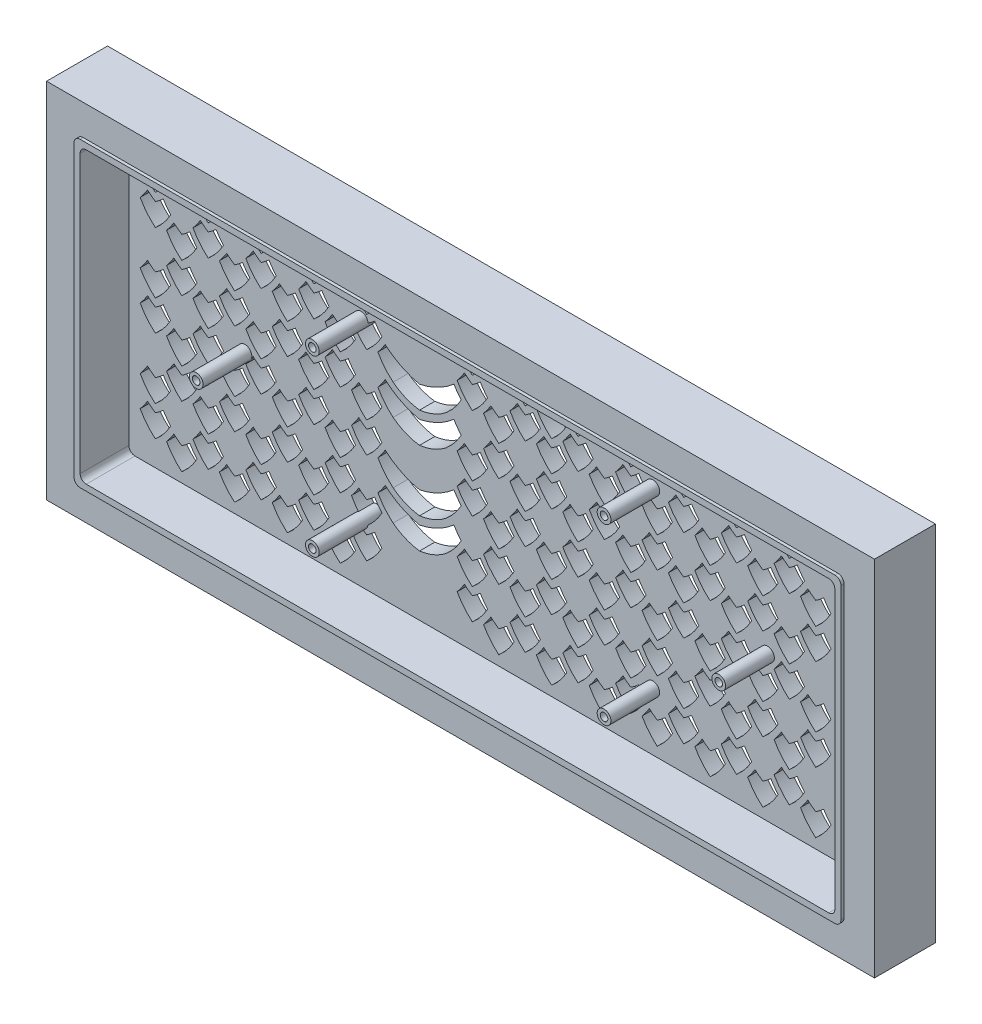
SolidWorks part; units mm, degrees
ref_plane "Front Plane" through (0, 0, 0) normal (0, 0, 1) x (1, 0, 0)
ref_plane "Top Plane" through (0, 0, 0) normal (0, 1, 0) x (1, 0, 0)
ref_plane "Right Plane" through (0, 0, 0) normal (1, 0, 0) x (0, 0, -1)
sketch "Sketch2" plane through (0, 0, 0) normal (0, 0, 1) x (1, 0, 0)
  line L2 (-123.825, 49.5056) -> (123.825, 49.5056)
  line L245 (-125.825, 47.5056) -> (-125.825, -47.5056)
  line L268 (-123.825, -49.5056) -> (123.825, -49.5056)
  line L269 (125.825, 47.5056) -> (125.825, -47.5056)
  line L270 (-125.825, 49.5056) -> (125.825, -49.5056) construction
  line L271 (-125.825, -49.5056) -> (125.825, 49.5056) construction
  arc A1 (-125.825, -47.5056) -> (-123.825, -49.5056) centre (-123.825, -47.5056) ccw
  arc A2 (123.825, -49.5056) -> (125.825, -47.5056) centre (123.825, -47.5056) ccw
  arc A3 (125.825, 47.5056) -> (123.825, 49.5056) centre (123.825, 47.5056) ccw
  arc A4 (-123.825, 49.5056) -> (-125.825, 47.5056) centre (-123.825, 47.5056) ccw
  circle A5 centre (-85.725, 0) radius 1.25
  circle A6 centre (85.725, 0) radius 1.25
  circle A7 centre (48.0908, -28.6944) radius 1.25
  circle A8 centre (48.0908, 28.4556) radius 1.25
  circle A9 centre (-47.625, 28.4556) radius 1.25
  circle A10 centre (-47.625, -28.6944) radius 1.25
  point P272 (0, 0)
  dimension "D1" = 2.5
sketch "Sketch4" plane through (0, 0, 0) normal (0, 0, 1) x (1, 0, 0)
  line L0 (119.825, 45.5056) -> (119.825, -45.5056) construction
  line L1 (-121.825, 47.5056) -> (121.825, 47.5056)
  line L2 (-123.825, 45.5056) -> (-123.825, -45.5056)
  line L3 (-121.825, -47.5056) -> (121.825, -47.5056)
  line L4 (123.825, 45.5056) -> (123.825, -45.5056)
  line L6 (-28.4483, 55.4845) -> (-28.4483, -112.1961) construction
  arc A78 (-71.789, -44.2969) -> (-76.7891, -38.2055) centre (-58.0044, -27.884) cw
  arc A79 (-76.7891, -38.2055) -> (-74.3831, -34.8729) centre (-95.5685, -22.1135) ccw
  arc A80 (-71.789, -36.876) -> (-74.3831, -34.8729) centre (-58.0044, -16.3429) cw
  arc A81 (-71.789, -36.876) -> (-69.1949, -34.8729) centre (-85.5736, -16.3429) ccw
  arc A82 (-66.7889, -38.2055) -> (-69.1949, -34.8729) centre (-48.0095, -22.1135) cw
  arc A83 (-71.789, -44.2969) -> (-66.7889, -38.2055) centre (-85.5736, -27.884) ccw
  arc A84 (-63.1222, -39.2931) -> (-68.1222, -33.2017) centre (-49.3376, -22.8802) cw
  arc A85 (-68.1222, -33.2017) -> (-65.7163, -29.8691) centre (-86.9017, -17.1097) ccw
  arc A86 (-63.1222, -31.8722) -> (-65.7163, -29.8691) centre (-49.3376, -11.3391) cw
  arc A87 (-63.1222, -31.8722) -> (-60.528, -29.8691) centre (-76.9067, -11.3391) ccw
  arc A88 (-58.1221, -33.2017) -> (-60.528, -29.8691) centre (-39.3427, -17.1097) cw
  arc A89 (-63.1222, -39.2931) -> (-58.1221, -33.2017) centre (-76.9067, -22.8802) ccw
  arc A108 (-89.1227, -44.2969) -> (-94.1227, -38.2055) centre (-75.3381, -27.884) cw
  arc A109 (-94.1227, -38.2055) -> (-91.7168, -34.8729) centre (-112.9022, -22.1135) ccw
  arc A110 (-89.1227, -36.876) -> (-91.7168, -34.8729) centre (-75.3381, -16.3429) cw
  arc A111 (-89.1227, -36.876) -> (-86.5285, -34.8729) centre (-102.9072, -16.3429) ccw
  arc A112 (-84.1226, -38.2055) -> (-86.5285, -34.8729) centre (-65.3432, -22.1135) cw
  arc A113 (-89.1227, -44.2969) -> (-84.1226, -38.2055) centre (-102.9072, -27.884) ccw
  arc A114 (-80.4558, -39.2931) -> (-85.4559, -33.2017) centre (-66.6712, -22.8802) cw
  arc A115 (-85.4559, -33.2017) -> (-83.05, -29.8691) centre (-104.2353, -17.1097) ccw
  arc A116 (-80.4558, -31.8722) -> (-83.05, -29.8691) centre (-66.6712, -11.3391) cw
  arc A117 (-80.4558, -31.8722) -> (-77.8617, -29.8691) centre (-94.2404, -11.3391) ccw
  arc A118 (-75.4558, -33.2017) -> (-77.8617, -29.8691) centre (-56.6763, -17.1097) cw
  arc A119 (-80.4558, -39.2931) -> (-75.4558, -33.2017) centre (-94.2404, -22.8802) ccw
  arc A126 (-63.1222, -29.2855) -> (-68.1222, -23.1941) centre (-49.3376, -12.8726) cw
  arc A127 (-68.1222, -23.1941) -> (-65.7163, -19.8615) centre (-86.9017, -7.1021) ccw
  arc A128 (-63.1222, -21.8646) -> (-65.7163, -19.8615) centre (-49.3376, -1.3315) cw
  arc A129 (-63.1222, -21.8646) -> (-60.528, -19.8615) centre (-76.9067, -1.3315) ccw
  arc A130 (-58.1221, -23.1941) -> (-60.528, -19.8615) centre (-39.3427, -7.1021) cw
  arc A131 (-63.1222, -29.2855) -> (-58.1221, -23.1941) centre (-76.9067, -12.8726) ccw
  arc A138 (-106.4563, -44.2969) -> (-111.4564, -38.2055) centre (-92.6718, -27.884) cw
  arc A139 (-111.4564, -38.2055) -> (-109.0505, -34.8729) centre (-130.2358, -22.1135) ccw
  arc A140 (-106.4563, -36.876) -> (-109.0505, -34.8729) centre (-92.6718, -16.3429) cw
  arc A141 (-106.4563, -36.876) -> (-103.8622, -34.8729) centre (-120.2409, -16.3429) ccw
  arc A142 (-101.4563, -38.2055) -> (-103.8622, -34.8729) centre (-82.6768, -22.1135) cw
  arc A143 (-106.4563, -44.2969) -> (-101.4563, -38.2055) centre (-120.2409, -27.884) ccw
  arc A144 (-97.7895, -39.2931) -> (-102.7896, -33.2017) centre (-84.0049, -22.8802) cw
  arc A145 (-102.7896, -33.2017) -> (-100.3836, -29.8691) centre (-121.569, -17.1097) ccw
  arc A146 (-97.7895, -31.8722) -> (-100.3836, -29.8691) centre (-84.0049, -11.3391) cw
  arc A147 (-97.7895, -31.8722) -> (-95.1954, -29.8691) centre (-111.5741, -11.3391) ccw
  arc A148 (-92.7894, -33.2017) -> (-95.1954, -29.8691) centre (-74.01, -17.1097) cw
  arc A149 (-97.7895, -39.2931) -> (-92.7894, -33.2017) centre (-111.5741, -22.8802) ccw
  arc A156 (-80.4558, -29.2855) -> (-85.4559, -23.1941) centre (-66.6712, -12.8726) cw
  arc A157 (-85.4559, -23.1941) -> (-83.05, -19.8615) centre (-104.2353, -7.1021) ccw
  arc A158 (-80.4558, -21.8646) -> (-83.05, -19.8615) centre (-66.6712, -1.3315) cw
  arc A159 (-80.4558, -21.8646) -> (-77.8617, -19.8615) centre (-94.2404, -1.3315) ccw
  arc A160 (-75.4558, -23.1941) -> (-77.8617, -19.8615) centre (-56.6763, -7.1021) cw
  arc A161 (-80.4558, -29.2855) -> (-75.4558, -23.1941) centre (-94.2404, -12.8726) ccw
  arc A162 (-71.789, -24.2817) -> (-76.7891, -18.1903) centre (-58.0044, -7.8688) cw
  arc A163 (-76.7891, -18.1903) -> (-74.3831, -14.8577) centre (-95.5685, -2.0983) ccw
  arc A164 (-71.789, -16.8608) -> (-74.3831, -14.8577) centre (-58.0044, 3.6723) cw
  arc A165 (-71.789, -16.8608) -> (-69.1949, -14.8577) centre (-85.5736, 3.6723) ccw
  arc A166 (-66.7889, -18.1903) -> (-69.1949, -14.8577) centre (-48.0095, -2.0983) cw
  arc A167 (-71.789, -24.2817) -> (-66.7889, -18.1903) centre (-85.5736, -7.8688) ccw
  arc A174 (-115.1232, -39.2931) -> (-120.1232, -33.2017) centre (-101.3386, -22.8802) cw
  arc A175 (-120.1232, -33.2017) -> (-117.7173, -29.8691) centre (-138.9027, -17.1097) ccw
  arc A176 (-115.1232, -31.8722) -> (-117.7173, -29.8691) centre (-101.3386, -11.3391) cw
  arc A177 (-115.1232, -31.8722) -> (-112.529, -29.8691) centre (-128.9078, -11.3391) ccw
  arc A178 (-110.1231, -33.2017) -> (-112.529, -29.8691) centre (-91.3437, -17.1097) cw
  arc A179 (-115.1232, -39.2931) -> (-110.1231, -33.2017) centre (-128.9078, -22.8802) ccw
  arc A186 (-97.7895, -29.2855) -> (-102.7896, -23.1941) centre (-84.0049, -12.8726) cw
  arc A187 (-102.7896, -23.1941) -> (-100.3836, -19.8615) centre (-121.569, -7.1021) ccw
  arc A188 (-97.7895, -21.8646) -> (-100.3836, -19.8615) centre (-84.0049, -1.3315) cw
  arc A189 (-97.7895, -21.8646) -> (-95.1954, -19.8615) centre (-111.5741, -1.3315) ccw
  arc A190 (-92.7894, -23.1941) -> (-95.1954, -19.8615) centre (-74.01, -7.1021) cw
  arc A191 (-97.7895, -29.2855) -> (-92.7894, -23.1941) centre (-111.5741, -12.8726) ccw
  arc A192 (-89.1227, -24.2817) -> (-94.1227, -18.1903) centre (-75.3381, -7.8688) cw
  arc A193 (-94.1227, -18.1903) -> (-91.7168, -14.8577) centre (-112.9022, -2.0983) ccw
  arc A194 (-89.1227, -16.8608) -> (-91.7168, -14.8577) centre (-75.3381, 3.6723) cw
  arc A195 (-89.1227, -16.8608) -> (-86.5285, -14.8577) centre (-102.9072, 3.6723) ccw
  arc A196 (-84.1226, -18.1903) -> (-86.5285, -14.8577) centre (-65.3432, -2.0983) cw
  arc A197 (-89.1227, -24.2817) -> (-84.1226, -18.1903) centre (-102.9072, -7.8688) ccw
  arc A204 (-71.789, -14.2741) -> (-76.7891, -8.1827) centre (-58.0044, 2.1388) cw
  arc A205 (-76.7891, -8.1827) -> (-74.3831, -4.8501) centre (-95.5685, 7.9093) ccw
  arc A206 (-71.789, -6.8532) -> (-74.3831, -4.8501) centre (-58.0044, 13.6799) cw
  arc A207 (-71.789, -6.8532) -> (-69.1949, -4.8501) centre (-85.5736, 13.6799) ccw
  arc A208 (-66.7889, -8.1827) -> (-69.1949, -4.8501) centre (-48.0095, 7.9093) cw
  arc A209 (-71.789, -14.2741) -> (-66.7889, -8.1827) centre (-85.5736, 2.1388) ccw
  arc A210 (-63.1222, -9.2703) -> (-68.1222, -3.1789) centre (-49.3376, 7.1426) cw
  arc A211 (-68.1222, -3.1789) -> (-65.7163, 0.1537) centre (-86.9017, 12.9131) ccw
  arc A212 (-63.1222, -1.8494) -> (-65.7163, 0.1537) centre (-49.3376, 18.6837) cw
  arc A213 (-63.1222, -1.8494) -> (-60.528, 0.1537) centre (-76.9067, 18.6837) ccw
  arc A214 (-58.1221, -3.1789) -> (-60.528, 0.1537) centre (-39.3427, 12.9131) cw
  arc A215 (-63.1222, -9.2703) -> (-58.1221, -3.1789) centre (-76.9067, 7.1426) ccw
  arc A216 (-115.1232, -29.2855) -> (-120.1232, -23.1941) centre (-101.3386, -12.8726) cw
  arc A217 (-120.1232, -23.1941) -> (-117.7173, -19.8615) centre (-138.9027, -7.1021) ccw
  arc A218 (-115.1232, -21.8646) -> (-117.7173, -19.8615) centre (-101.3386, -1.3315) cw
  arc A219 (-115.1232, -21.8646) -> (-112.529, -19.8615) centre (-128.9078, -1.3315) ccw
  arc A220 (-110.1231, -23.1941) -> (-112.529, -19.8615) centre (-91.3437, -7.1021) cw
  arc A221 (-115.1232, -29.2855) -> (-110.1231, -23.1941) centre (-128.9078, -12.8726) ccw
  arc A222 (-106.4563, -24.2817) -> (-111.4564, -18.1903) centre (-92.6718, -7.8688) cw
  arc A223 (-111.4564, -18.1903) -> (-109.0505, -14.8577) centre (-130.2358, -2.0983) ccw
  arc A224 (-106.4563, -16.8608) -> (-109.0505, -14.8577) centre (-92.6718, 3.6723) cw
  arc A225 (-106.4563, -16.8608) -> (-103.8622, -14.8577) centre (-120.2409, 3.6723) ccw
  arc A226 (-101.4563, -18.1903) -> (-103.8622, -14.8577) centre (-82.6768, -2.0983) cw
  arc A227 (-106.4563, -24.2817) -> (-101.4563, -18.1903) centre (-120.2409, -7.8688) ccw
  arc A234 (-89.1227, -14.2741) -> (-94.1227, -8.1827) centre (-75.3381, 2.1388) cw
  arc A235 (-94.1227, -8.1827) -> (-91.7168, -4.8501) centre (-112.9022, 7.9093) ccw
  arc A236 (-89.1227, -6.8532) -> (-91.7168, -4.8501) centre (-75.3381, 13.6799) cw
  arc A237 (-89.1227, -6.8532) -> (-86.5285, -4.8501) centre (-102.9072, 13.6799) ccw
  arc A238 (-84.1226, -8.1827) -> (-86.5285, -4.8501) centre (-65.3432, 7.9093) cw
  arc A239 (-89.1227, -14.2741) -> (-84.1226, -8.1827) centre (-102.9072, 2.1388) ccw
  arc A240 (-80.4558, -9.2703) -> (-85.4559, -3.1789) centre (-66.6712, 7.1426) cw
  arc A241 (-85.4559, -3.1789) -> (-83.05, 0.1537) centre (-104.2353, 12.9131) ccw
  arc A242 (-80.4558, -1.8494) -> (-83.05, 0.1537) centre (-66.6712, 18.6837) cw
  arc A243 (-80.4558, -1.8494) -> (-77.8617, 0.1537) centre (-94.2404, 18.6837) ccw
  arc A244 (-75.4558, -3.1789) -> (-77.8617, 0.1537) centre (-56.6763, 12.9131) cw
  arc A245 (-80.4558, -9.2703) -> (-75.4558, -3.1789) centre (-94.2404, 7.1426) ccw
  arc A252 (-63.1222, 0.7373) -> (-68.1222, 6.8287) centre (-49.3376, 17.1502) cw
  arc A253 (-68.1222, 6.8287) -> (-65.7163, 10.1613) centre (-86.9017, 22.9207) ccw
  arc A254 (-63.1222, 8.1582) -> (-65.7163, 10.1613) centre (-49.3376, 28.6913) cw
  arc A255 (-63.1222, 8.1582) -> (-60.528, 10.1613) centre (-76.9067, 28.6913) ccw
  arc A256 (-58.1221, 6.8287) -> (-60.528, 10.1613) centre (-39.3427, 22.9207) cw
  arc A257 (-63.1222, 0.7373) -> (-58.1221, 6.8287) centre (-76.9067, 17.1502) ccw
  arc A264 (-106.4563, -14.2741) -> (-111.4564, -8.1827) centre (-92.6718, 2.1388) cw
  arc A265 (-111.4564, -8.1827) -> (-109.0505, -4.8501) centre (-130.2358, 7.9093) ccw
  arc A266 (-106.4563, -6.8532) -> (-109.0505, -4.8501) centre (-92.6718, 13.6799) cw
  arc A267 (-106.4563, -6.8532) -> (-103.8622, -4.8501) centre (-120.2409, 13.6799) ccw
  arc A268 (-101.4563, -8.1827) -> (-103.8622, -4.8501) centre (-82.6768, 7.9093) cw
  arc A269 (-106.4563, -14.2741) -> (-101.4563, -8.1827) centre (-120.2409, 2.1388) ccw
  arc A270 (-97.7895, -9.2703) -> (-102.7896, -3.1789) centre (-84.0049, 7.1426) cw
  arc A271 (-102.7896, -3.1789) -> (-100.3836, 0.1537) centre (-121.569, 12.9131) ccw
  arc A272 (-97.7895, -1.8494) -> (-100.3836, 0.1537) centre (-84.0049, 18.6837) cw
  arc A273 (-97.7895, -1.8494) -> (-95.1954, 0.1537) centre (-111.5741, 18.6837) ccw
  arc A274 (-92.7894, -3.1789) -> (-95.1954, 0.1537) centre (-74.01, 12.9131) cw
  arc A275 (-97.7895, -9.2703) -> (-92.7894, -3.1789) centre (-111.5741, 7.1426) ccw
  arc A282 (-80.4558, 0.7373) -> (-85.4559, 6.8287) centre (-66.6712, 17.1502) cw
  arc A283 (-85.4559, 6.8287) -> (-83.05, 10.1613) centre (-104.2353, 22.9207) ccw
  arc A284 (-80.4558, 8.1582) -> (-83.05, 10.1613) centre (-66.6712, 28.6913) cw
  arc A285 (-80.4558, 8.1582) -> (-77.8617, 10.1613) centre (-94.2404, 28.6913) ccw
  arc A286 (-75.4558, 6.8287) -> (-77.8617, 10.1613) centre (-56.6763, 22.9207) cw
  arc A287 (-80.4558, 0.7373) -> (-75.4558, 6.8287) centre (-94.2404, 17.1502) ccw
  arc A288 (-71.789, 5.7411) -> (-76.7891, 11.8325) centre (-58.0044, 22.154) cw
  arc A289 (-76.7891, 11.8325) -> (-74.3831, 15.1651) centre (-95.5685, 27.9245) ccw
  arc A290 (-71.789, 13.162) -> (-74.3831, 15.1651) centre (-58.0044, 33.6951) cw
  arc A291 (-71.789, 13.162) -> (-69.1949, 15.1651) centre (-85.5736, 33.6951) ccw
  arc A292 (-66.7889, 11.8325) -> (-69.1949, 15.1651) centre (-48.0095, 27.9245) cw
  arc A293 (-71.789, 5.7411) -> (-66.7889, 11.8325) centre (-85.5736, 22.154) ccw
  arc A300 (-115.1232, -9.2703) -> (-120.1232, -3.1789) centre (-101.3386, 7.1426) cw
  arc A301 (-120.1232, -3.1789) -> (-117.7173, 0.1537) centre (-138.9027, 12.9131) ccw
  arc A302 (-115.1232, -1.8494) -> (-117.7173, 0.1537) centre (-101.3386, 18.6837) cw
  arc A303 (-115.1232, -1.8494) -> (-112.529, 0.1537) centre (-128.9078, 18.6837) ccw
  arc A304 (-110.1231, -3.1789) -> (-112.529, 0.1537) centre (-91.3437, 12.9131) cw
  arc A305 (-115.1232, -9.2703) -> (-110.1231, -3.1789) centre (-128.9078, 7.1426) ccw
  arc A312 (-97.7895, 0.7373) -> (-102.7896, 6.8287) centre (-84.0049, 17.1502) cw
  arc A313 (-102.7896, 6.8287) -> (-100.3836, 10.1613) centre (-121.569, 22.9207) ccw
  arc A314 (-97.7895, 8.1582) -> (-100.3836, 10.1613) centre (-84.0049, 28.6913) cw
  arc A315 (-97.7895, 8.1582) -> (-95.1954, 10.1613) centre (-111.5741, 28.6913) ccw
  arc A316 (-92.7894, 6.8287) -> (-95.1954, 10.1613) centre (-74.01, 22.9207) cw
  arc A317 (-97.7895, 0.7373) -> (-92.7894, 6.8287) centre (-111.5741, 17.1502) ccw
  arc A318 (-89.1227, 5.7411) -> (-94.1227, 11.8325) centre (-75.3381, 22.154) cw
  arc A319 (-94.1227, 11.8325) -> (-91.7168, 15.1651) centre (-112.9022, 27.9245) ccw
  arc A320 (-89.1227, 13.162) -> (-91.7168, 15.1651) centre (-75.3381, 33.6951) cw
  arc A321 (-89.1227, 13.162) -> (-86.5285, 15.1651) centre (-102.9072, 33.6951) ccw
  arc A322 (-84.1226, 11.8325) -> (-86.5285, 15.1651) centre (-65.3432, 27.9245) cw
  arc A323 (-89.1227, 5.7411) -> (-84.1226, 11.8325) centre (-102.9072, 22.154) ccw
  arc A330 (-71.789, 15.7487) -> (-76.7891, 21.8401) centre (-58.0044, 32.1616) cw
  arc A331 (-76.7891, 21.8401) -> (-74.3831, 25.1727) centre (-95.5685, 37.9321) ccw
  arc A332 (-71.789, 23.1696) -> (-74.3831, 25.1727) centre (-58.0044, 43.7027) cw
  arc A333 (-71.789, 23.1696) -> (-69.1949, 25.1727) centre (-85.5736, 43.7027) ccw
  arc A334 (-66.7889, 21.8401) -> (-69.1949, 25.1727) centre (-48.0095, 37.9321) cw
  arc A335 (-71.789, 15.7487) -> (-66.7889, 21.8401) centre (-85.5736, 32.1616) ccw
  arc A336 (-63.1222, 20.7525) -> (-68.1222, 26.8439) centre (-49.3376, 37.1654) cw
  arc A337 (-68.1222, 26.8439) -> (-65.7163, 30.1765) centre (-86.9017, 42.9359) ccw
  arc A338 (-63.1222, 28.1734) -> (-65.7163, 30.1765) centre (-49.3376, 48.7065) cw
  arc A339 (-63.1222, 28.1734) -> (-60.528, 30.1765) centre (-76.9067, 48.7065) ccw
  arc A340 (-58.1221, 26.8439) -> (-60.528, 30.1765) centre (-39.3427, 42.9359) cw
  arc A341 (-63.1222, 20.7525) -> (-58.1221, 26.8439) centre (-76.9067, 37.1654) ccw
  arc A342 (-115.1232, 0.7373) -> (-120.1232, 6.8287) centre (-101.3386, 17.1502) cw
  arc A343 (-120.1232, 6.8287) -> (-117.7173, 10.1613) centre (-138.9027, 22.9207) ccw
  arc A344 (-115.1232, 8.1582) -> (-117.7173, 10.1613) centre (-101.3386, 28.6913) cw
  arc A345 (-115.1232, 8.1582) -> (-112.529, 10.1613) centre (-128.9078, 28.6913) ccw
  arc A346 (-110.1231, 6.8287) -> (-112.529, 10.1613) centre (-91.3437, 22.9207) cw
  arc A347 (-115.1232, 0.7373) -> (-110.1231, 6.8287) centre (-128.9078, 17.1502) ccw
  arc A348 (-106.4563, 5.7411) -> (-111.4564, 11.8325) centre (-92.6718, 22.154) cw
  arc A349 (-111.4564, 11.8325) -> (-109.0505, 15.1651) centre (-130.2358, 27.9245) ccw
  arc A350 (-106.4563, 13.162) -> (-109.0505, 15.1651) centre (-92.6718, 33.6951) cw
  arc A351 (-106.4563, 13.162) -> (-103.8622, 15.1651) centre (-120.2409, 33.6951) ccw
  arc A352 (-101.4563, 11.8325) -> (-103.8622, 15.1651) centre (-82.6768, 27.9245) cw
  arc A353 (-106.4563, 5.7411) -> (-101.4563, 11.8325) centre (-120.2409, 22.154) ccw
  arc A360 (-89.1227, 15.7487) -> (-94.1227, 21.8401) centre (-75.3381, 32.1616) cw
  arc A361 (-94.1227, 21.8401) -> (-91.7168, 25.1727) centre (-112.9022, 37.9321) ccw
  arc A362 (-89.1227, 23.1696) -> (-91.7168, 25.1727) centre (-75.3381, 43.7027) cw
  arc A363 (-89.1227, 23.1696) -> (-86.5285, 25.1727) centre (-102.9072, 43.7027) ccw
  arc A364 (-84.1226, 21.8401) -> (-86.5285, 25.1727) centre (-65.3432, 37.9321) cw
  arc A365 (-89.1227, 15.7487) -> (-84.1226, 21.8401) centre (-102.9072, 32.1616) ccw
  arc A366 (-80.4558, 20.7525) -> (-85.4559, 26.8439) centre (-66.6712, 37.1654) cw
  arc A367 (-85.4559, 26.8439) -> (-83.05, 30.1765) centre (-104.2353, 42.9359) ccw
  arc A368 (-80.4558, 28.1734) -> (-83.05, 30.1765) centre (-66.6712, 48.7065) cw
  arc A369 (-80.4558, 28.1734) -> (-77.8617, 30.1765) centre (-94.2404, 48.7065) ccw
  arc A370 (-75.4558, 26.8439) -> (-77.8617, 30.1765) centre (-56.6763, 42.9359) cw
  arc A371 (-80.4558, 20.7525) -> (-75.4558, 26.8439) centre (-94.2404, 37.1654) ccw
  arc A378 (-63.1222, 30.7601) -> (-68.1222, 36.8515) centre (-49.3376, 47.173) cw
  arc A379 (-68.1222, 36.8515) -> (-65.7163, 40.1841) centre (-86.9017, 52.9435) ccw
  arc A380 (-63.1222, 38.181) -> (-65.7163, 40.1841) centre (-49.3376, 58.7141) cw
  arc A381 (-63.1222, 38.181) -> (-60.528, 40.1841) centre (-76.9067, 58.7141) ccw
  arc A382 (-58.1221, 36.8515) -> (-60.528, 40.1841) centre (-39.3427, 52.9435) cw
  arc A383 (-63.1222, 30.7601) -> (-58.1221, 36.8515) centre (-76.9067, 47.173) ccw
  arc A390 (-106.4563, 15.7487) -> (-111.4564, 21.8401) centre (-92.6718, 32.1616) cw
  arc A391 (-111.4564, 21.8401) -> (-109.0505, 25.1727) centre (-130.2358, 37.9321) ccw
  arc A392 (-106.4563, 23.1696) -> (-109.0505, 25.1727) centre (-92.6718, 43.7027) cw
  arc A393 (-106.4563, 23.1696) -> (-103.8622, 25.1727) centre (-120.2409, 43.7027) ccw
  arc A394 (-101.4563, 21.8401) -> (-103.8622, 25.1727) centre (-82.6768, 37.9321) cw
  arc A395 (-106.4563, 15.7487) -> (-101.4563, 21.8401) centre (-120.2409, 32.1616) ccw
  arc A396 (-97.7895, 20.7525) -> (-102.7896, 26.8439) centre (-84.0049, 37.1654) cw
  arc A397 (-102.7896, 26.8439) -> (-100.3836, 30.1765) centre (-121.569, 42.9359) ccw
  arc A398 (-97.7895, 28.1734) -> (-100.3836, 30.1765) centre (-84.0049, 48.7065) cw
  arc A399 (-97.7895, 28.1734) -> (-95.1954, 30.1765) centre (-111.5741, 48.7065) ccw
  arc A400 (-92.7894, 26.8439) -> (-95.1954, 30.1765) centre (-74.01, 42.9359) cw
  arc A401 (-97.7895, 20.7525) -> (-92.7894, 26.8439) centre (-111.5741, 37.1654) ccw
  arc A408 (-80.4558, 30.7601) -> (-85.4559, 36.8515) centre (-66.6712, 47.173) cw
  arc A409 (-85.4559, 36.8515) -> (-83.05, 40.1841) centre (-104.2353, 52.9435) ccw
  arc A410 (-80.4558, 38.181) -> (-83.05, 40.1841) centre (-66.6712, 58.7141) cw
  arc A411 (-80.4558, 38.181) -> (-77.8617, 40.1841) centre (-94.2404, 58.7141) ccw
  arc A412 (-75.4558, 36.8515) -> (-77.8617, 40.1841) centre (-56.6763, 52.9435) cw
  arc A413 (-80.4558, 30.7601) -> (-75.4558, 36.8515) centre (-94.2404, 47.173) ccw
  arc A414 (-71.789, 35.7639) -> (-76.7891, 41.8553) centre (-58.0044, 52.1768) cw
  arc A415 (-76.7891, 41.8553) -> (-74.3831, 45.1879) centre (-95.5685, 57.9473) ccw
  arc A416 (-71.789, 43.1848) -> (-74.3831, 45.1879) centre (-58.0044, 63.7179) cw
  arc A417 (-71.789, 43.1848) -> (-69.1949, 45.1879) centre (-85.5736, 63.7179) ccw
  arc A418 (-66.7889, 41.8553) -> (-69.1949, 45.1879) centre (-48.0095, 57.9473) cw
  arc A419 (-71.789, 35.7639) -> (-66.7889, 41.8553) centre (-85.5736, 52.1768) ccw
  arc A426 (-115.1232, 20.7525) -> (-120.1232, 26.8439) centre (-101.3386, 37.1654) cw
  arc A427 (-120.1232, 26.8439) -> (-117.7173, 30.1765) centre (-138.9027, 42.9359) ccw
  arc A428 (-115.1232, 28.1734) -> (-117.7173, 30.1765) centre (-101.3386, 48.7065) cw
  arc A429 (-115.1232, 28.1734) -> (-112.529, 30.1765) centre (-128.9078, 48.7065) ccw
  arc A430 (-110.1231, 26.8439) -> (-112.529, 30.1765) centre (-91.3437, 42.9359) cw
  arc A431 (-115.1232, 20.7525) -> (-110.1231, 26.8439) centre (-128.9078, 37.1654) ccw
  arc A438 (-97.7895, 30.7601) -> (-102.7896, 36.8515) centre (-84.0049, 47.173) cw
  arc A439 (-102.7896, 36.8515) -> (-100.3836, 40.1841) centre (-121.569, 52.9435) ccw
  arc A440 (-97.7895, 38.181) -> (-100.3836, 40.1841) centre (-84.0049, 58.7141) cw
  arc A441 (-97.7895, 38.181) -> (-95.1954, 40.1841) centre (-111.5741, 58.7141) ccw
  arc A442 (-92.7894, 36.8515) -> (-95.1954, 40.1841) centre (-74.01, 52.9435) cw
  arc A443 (-97.7895, 30.7601) -> (-92.7894, 36.8515) centre (-111.5741, 47.173) ccw
  arc A444 (-89.1227, 35.7639) -> (-94.1227, 41.8553) centre (-75.3381, 52.1768) cw
  arc A445 (-94.1227, 41.8553) -> (-91.7168, 45.1879) centre (-112.9022, 57.9473) ccw
  arc A446 (-89.1227, 43.1848) -> (-91.7168, 45.1879) centre (-75.3381, 63.7179) cw
  arc A447 (-89.1227, 43.1848) -> (-86.5285, 45.1879) centre (-102.9072, 63.7179) ccw
  arc A448 (-84.1226, 41.8553) -> (-86.5285, 45.1879) centre (-65.3432, 57.9473) cw
  arc A449 (-89.1227, 35.7639) -> (-84.1226, 41.8553) centre (-102.9072, 52.1768) ccw
  arc A468 (-115.1232, 30.7601) -> (-120.1232, 36.8515) centre (-101.3386, 47.173) cw
  arc A469 (-120.1232, 36.8515) -> (-117.7173, 40.1841) centre (-138.9027, 52.9435) ccw
  arc A470 (-115.1232, 38.181) -> (-117.7173, 40.1841) centre (-101.3386, 58.7141) cw
  arc A471 (-115.1232, 38.181) -> (-112.529, 40.1841) centre (-128.9078, 58.7141) ccw
  arc A472 (-110.1231, 36.8515) -> (-112.529, 40.1841) centre (-91.3437, 52.9435) cw
  arc A473 (-115.1232, 30.7601) -> (-110.1231, 36.8515) centre (-128.9078, 47.173) ccw
  arc A474 (-106.4563, 35.7639) -> (-111.4564, 41.8553) centre (-92.6718, 52.1768) cw
  arc A475 (-111.4564, 41.8553) -> (-109.0505, 45.1879) centre (-130.2358, 57.9473) ccw
  arc A476 (-106.4563, 43.1848) -> (-109.0505, 45.1879) centre (-92.6718, 63.7179) cw
  arc A477 (-106.4563, 43.1848) -> (-103.8622, 45.1879) centre (-120.2409, 63.7179) ccw
  arc A478 (-101.4563, 41.8553) -> (-103.8622, 45.1879) centre (-82.6768, 57.9473) cw
  arc A479 (-106.4563, 35.7639) -> (-101.4563, 41.8553) centre (-120.2409, 52.1768) ccw
  arc A888 (66.8804, -44.2969) -> (61.8803, -38.2055) centre (80.665, -27.884) cw
  arc A889 (61.8803, -38.2055) -> (64.2863, -34.8729) centre (43.1009, -22.1135) ccw
  arc A890 (66.8804, -36.876) -> (64.2863, -34.8729) centre (80.665, -16.3429) cw
  arc A891 (66.8804, -36.876) -> (69.4745, -34.8729) centre (53.0958, -16.3429) ccw
  arc A892 (71.8804, -38.2055) -> (69.4745, -34.8729) centre (90.6599, -22.1135) cw
  arc A893 (66.8804, -44.2969) -> (71.8804, -38.2055) centre (53.0958, -27.884) ccw
  arc A894 (75.5472, -39.2931) -> (70.5472, -33.2017) centre (89.3318, -22.8802) cw
  arc A895 (70.5472, -33.2017) -> (72.9531, -29.8691) centre (51.7677, -17.1097) ccw
  arc A896 (75.5472, -31.8722) -> (72.9531, -29.8691) centre (89.3318, -11.3391) cw
  arc A897 (75.5472, -31.8722) -> (78.1413, -29.8691) centre (61.7626, -11.3391) ccw
  arc A898 (80.5473, -33.2017) -> (78.1413, -29.8691) centre (99.3267, -17.1097) cw
  arc A899 (75.5472, -39.2931) -> (80.5473, -33.2017) centre (61.7626, -22.8802) ccw
  arc A966 (49.5467, -44.2969) -> (44.5467, -38.2055) centre (63.3313, -27.884) cw
  arc A967 (44.5467, -38.2055) -> (46.9526, -34.8729) centre (25.7672, -22.1135) ccw
  arc A968 (49.5467, -36.876) -> (46.9526, -34.8729) centre (63.3313, -16.3429) cw
  arc A969 (49.5467, -36.876) -> (52.1408, -34.8729) centre (35.7621, -16.3429) ccw
  arc A970 (54.5468, -38.2055) -> (52.1408, -34.8729) centre (73.3262, -22.1135) cw
  arc A971 (49.5467, -44.2969) -> (54.5468, -38.2055) centre (35.7621, -27.884) ccw
  arc A972 (58.2135, -39.2931) -> (53.2135, -33.2017) centre (71.9981, -22.8802) cw
  arc A973 (53.2135, -33.2017) -> (55.6194, -29.8691) centre (34.434, -17.1097) ccw
  arc A974 (58.2135, -31.8722) -> (55.6194, -29.8691) centre (71.9981, -11.3391) cw
  arc A975 (58.2135, -31.8722) -> (60.8077, -29.8691) centre (44.429, -11.3391) ccw
  arc A976 (63.2136, -33.2017) -> (60.8077, -29.8691) centre (81.993, -17.1097) cw
  arc A977 (58.2135, -39.2931) -> (63.2136, -33.2017) centre (44.429, -22.8802) ccw
  arc A984 (75.5472, -29.2855) -> (70.5472, -23.1941) centre (89.3318, -12.8726) cw
  arc A985 (70.5472, -23.1941) -> (72.9531, -19.8615) centre (51.7677, -7.1021) ccw
  arc A986 (75.5472, -21.8646) -> (72.9531, -19.8615) centre (89.3318, -1.3315) cw
  arc A987 (75.5472, -21.8646) -> (78.1413, -19.8615) centre (61.7626, -1.3315) ccw
  arc A988 (80.5473, -23.1941) -> (78.1413, -19.8615) centre (99.3267, -7.1021) cw
  arc A989 (75.5472, -29.2855) -> (80.5473, -23.1941) centre (61.7626, -12.8726) ccw
  arc A1044 (32.213, -44.2969) -> (27.213, -38.2055) centre (45.9976, -27.884) cw
  arc A1045 (27.213, -38.2055) -> (29.6189, -34.8729) centre (8.4335, -22.1135) ccw
  arc A1046 (32.213, -36.876) -> (29.6189, -34.8729) centre (45.9976, -16.3429) cw
  arc A1047 (32.213, -36.876) -> (34.8072, -34.8729) centre (18.4285, -16.3429) ccw
  arc A1048 (37.2131, -38.2055) -> (34.8072, -34.8729) centre (55.9925, -22.1135) cw
  arc A1049 (32.213, -44.2969) -> (37.2131, -38.2055) centre (18.4285, -27.884) ccw
  arc A1050 (40.8799, -39.2931) -> (35.8798, -33.2017) centre (54.6645, -22.8802) cw
  arc A1051 (35.8798, -33.2017) -> (38.2857, -29.8691) centre (17.1004, -17.1097) ccw
  arc A1052 (40.8799, -31.8722) -> (38.2857, -29.8691) centre (54.6645, -11.3391) cw
  arc A1053 (40.8799, -31.8722) -> (43.474, -29.8691) centre (27.0953, -11.3391) ccw
  arc A1054 (45.8799, -33.2017) -> (43.474, -29.8691) centre (64.6594, -17.1097) cw
  arc A1055 (40.8799, -39.2931) -> (45.8799, -33.2017) centre (27.0953, -22.8802) ccw
  arc A1062 (58.2135, -29.2855) -> (53.2135, -23.1941) centre (71.9981, -12.8726) cw
  arc A1063 (53.2135, -23.1941) -> (55.6194, -19.8615) centre (34.434, -7.1021) ccw
  arc A1064 (58.2135, -21.8646) -> (55.6194, -19.8615) centre (71.9981, -1.3315) cw
  arc A1065 (58.2135, -21.8646) -> (60.8077, -19.8615) centre (44.429, -1.3315) ccw
  arc A1066 (63.2136, -23.1941) -> (60.8077, -19.8615) centre (81.993, -7.1021) cw
  arc A1067 (58.2135, -29.2855) -> (63.2136, -23.1941) centre (44.429, -12.8726) ccw
  arc A1068 (66.8804, -24.2817) -> (61.8803, -18.1903) centre (80.665, -7.8688) cw
  arc A1069 (61.8803, -18.1903) -> (64.2863, -14.8577) centre (43.1009, -2.0983) ccw
  arc A1070 (66.8804, -16.8608) -> (64.2863, -14.8577) centre (80.665, 3.6723) cw
  arc A1071 (66.8804, -16.8608) -> (69.4745, -14.8577) centre (53.0958, 3.6723) ccw
  arc A1072 (71.8804, -18.1903) -> (69.4745, -14.8577) centre (90.6599, -2.0983) cw
  arc A1073 (66.8804, -24.2817) -> (71.8804, -18.1903) centre (53.0958, -7.8688) ccw
  arc A1122 (14.8794, -44.2969) -> (9.8793, -38.2055) centre (28.664, -27.884) cw
  arc A1123 (9.8793, -38.2055) -> (12.2852, -34.8729) centre (-8.9001, -22.1135) ccw
  arc A1124 (14.8794, -36.876) -> (12.2852, -34.8729) centre (28.664, -16.3429) cw
  arc A1125 (14.8794, -36.876) -> (17.4735, -34.8729) centre (1.0948, -16.3429) ccw
  arc A1126 (19.8794, -38.2055) -> (17.4735, -34.8729) centre (38.6589, -22.1135) cw
  arc A1127 (14.8794, -44.2969) -> (19.8794, -38.2055) centre (1.0948, -27.884) ccw
  arc A1128 (23.5462, -39.2931) -> (18.5461, -33.2017) centre (37.3308, -22.8802) cw
  arc A1129 (18.5461, -33.2017) -> (20.9521, -29.8691) centre (-0.2333, -17.1097) ccw
  arc A1130 (23.5462, -31.8722) -> (20.9521, -29.8691) centre (37.3308, -11.3391) cw
  arc A1131 (23.5462, -31.8722) -> (26.1403, -29.8691) centre (9.7616, -11.3391) ccw
  arc A1132 (28.5463, -33.2017) -> (26.1403, -29.8691) centre (47.3257, -17.1097) cw
  arc A1133 (23.5462, -39.2931) -> (28.5463, -33.2017) centre (9.7616, -22.8802) ccw
  arc A1140 (40.8799, -29.2855) -> (35.8798, -23.1941) centre (54.6645, -12.8726) cw
  arc A1141 (35.8798, -23.1941) -> (38.2857, -19.8615) centre (17.1004, -7.1021) ccw
  arc A1142 (40.8799, -21.8646) -> (38.2857, -19.8615) centre (54.6645, -1.3315) cw
  arc A1143 (40.8799, -21.8646) -> (43.474, -19.8615) centre (27.0953, -1.3315) ccw
  arc A1144 (45.8799, -23.1941) -> (43.474, -19.8615) centre (64.6594, -7.1021) cw
  arc A1145 (40.8799, -29.2855) -> (45.8799, -23.1941) centre (27.0953, -12.8726) ccw
  arc A1146 (49.5467, -24.2817) -> (44.5467, -18.1903) centre (63.3313, -7.8688) cw
  arc A1147 (44.5467, -18.1903) -> (46.9526, -14.8577) centre (25.7672, -2.0983) ccw
  arc A1148 (49.5467, -16.8608) -> (46.9526, -14.8577) centre (63.3313, 3.6723) cw
  arc A1149 (49.5467, -16.8608) -> (52.1408, -14.8577) centre (35.7621, 3.6723) ccw
  arc A1150 (54.5468, -18.1903) -> (52.1408, -14.8577) centre (73.3262, -2.0983) cw
  arc A1151 (49.5467, -24.2817) -> (54.5468, -18.1903) centre (35.7621, -7.8688) ccw
  arc A1158 (66.8804, -14.2741) -> (61.8803, -8.1827) centre (80.665, 2.1388) cw
  arc A1159 (61.8803, -8.1827) -> (64.2863, -4.8501) centre (43.1009, 7.9093) ccw
  arc A1160 (66.8804, -6.8532) -> (64.2863, -4.8501) centre (80.665, 13.6799) cw
  arc A1161 (66.8804, -6.8532) -> (69.4745, -4.8501) centre (53.0958, 13.6799) ccw
  arc A1162 (71.8804, -8.1827) -> (69.4745, -4.8501) centre (90.6599, 7.9093) cw
  arc A1163 (66.8804, -14.2741) -> (71.8804, -8.1827) centre (53.0958, 2.1388) ccw
  arc A1164 (75.5472, -9.2703) -> (70.5472, -3.1789) centre (89.3318, 7.1426) cw
  arc A1165 (70.5472, -3.1789) -> (72.9531, 0.1537) centre (51.7677, 12.9131) ccw
  arc A1166 (75.5472, -1.8494) -> (72.9531, 0.1537) centre (89.3318, 18.6837) cw
  arc A1167 (75.5472, -1.8494) -> (78.1413, 0.1537) centre (61.7626, 18.6837) ccw
  arc A1168 (80.5473, -3.1789) -> (78.1413, 0.1537) centre (99.3267, 12.9131) cw
  arc A1169 (75.5472, -9.2703) -> (80.5473, -3.1789) centre (61.7626, 7.1426) ccw
  arc A1200 (-2.4543, -44.2969) -> (-7.4544, -38.2055) centre (11.3303, -27.884) cw
  arc A1201 (-7.4544, -38.2055) -> (-5.0484, -34.8729) centre (-26.2338, -22.1135) ccw
  arc A1202 (-2.4543, -36.876) -> (-5.0484, -34.8729) centre (11.3303, -16.3429) cw
  arc A1203 (-2.4543, -36.876) -> (0.1398, -34.8729) centre (-16.2389, -16.3429) ccw
  arc A1204 (2.5458, -38.2055) -> (0.1398, -34.8729) centre (21.3252, -22.1135) cw
  arc A1205 (-2.4543, -44.2969) -> (2.5458, -38.2055) centre (-16.2389, -27.884) ccw
  arc A1206 (6.2125, -39.2931) -> (1.2125, -33.2017) centre (19.9971, -22.8802) cw
  arc A1207 (1.2125, -33.2017) -> (3.6184, -29.8691) centre (-17.567, -17.1097) ccw
  arc A1208 (6.2125, -31.8722) -> (3.6184, -29.8691) centre (19.9971, -11.3391) cw
  arc A1209 (6.2125, -31.8722) -> (8.8067, -29.8691) centre (-7.5721, -11.3391) ccw
  arc A1210 (11.2126, -33.2017) -> (8.8067, -29.8691) centre (29.992, -17.1097) cw
  arc A1211 (6.2125, -39.2931) -> (11.2126, -33.2017) centre (-7.5721, -22.8802) ccw
  arc A1218 (23.5462, -29.2855) -> (18.5461, -23.1941) centre (37.3308, -12.8726) cw
  arc A1219 (18.5461, -23.1941) -> (20.9521, -19.8615) centre (-0.2333, -7.1021) ccw
  arc A1220 (23.5462, -21.8646) -> (20.9521, -19.8615) centre (37.3308, -1.3315) cw
  arc A1221 (23.5462, -21.8646) -> (26.1403, -19.8615) centre (9.7616, -1.3315) ccw
  arc A1222 (28.5463, -23.1941) -> (26.1403, -19.8615) centre (47.3257, -7.1021) cw
  arc A1223 (23.5462, -29.2855) -> (28.5463, -23.1941) centre (9.7616, -12.8726) ccw
  arc A1224 (32.213, -24.2817) -> (27.213, -18.1903) centre (45.9976, -7.8688) cw
  arc A1225 (27.213, -18.1903) -> (29.6189, -14.8577) centre (8.4335, -2.0983) ccw
  arc A1226 (32.213, -16.8608) -> (29.6189, -14.8577) centre (45.9976, 3.6723) cw
  arc A1227 (32.213, -16.8608) -> (34.8072, -14.8577) centre (18.4285, 3.6723) ccw
  arc A1228 (37.2131, -18.1903) -> (34.8072, -14.8577) centre (55.9925, -2.0983) cw
  arc A1229 (32.213, -24.2817) -> (37.2131, -18.1903) centre (18.4285, -7.8688) ccw
  arc A1236 (49.5467, -14.2741) -> (44.5467, -8.1827) centre (63.3313, 2.1388) cw
  arc A1237 (44.5467, -8.1827) -> (46.9526, -4.8501) centre (25.7672, 7.9093) ccw
  arc A1238 (49.5467, -6.8532) -> (46.9526, -4.8501) centre (63.3313, 13.6799) cw
  arc A1239 (49.5467, -6.8532) -> (52.1408, -4.8501) centre (35.7621, 13.6799) ccw
  arc A1240 (54.5468, -8.1827) -> (52.1408, -4.8501) centre (73.3262, 7.9093) cw
  arc A1241 (49.5467, -14.2741) -> (54.5468, -8.1827) centre (35.7621, 2.1388) ccw
  arc A1242 (58.2135, -9.2703) -> (53.2135, -3.1789) centre (71.9981, 7.1426) cw
  arc A1243 (53.2135, -3.1789) -> (55.6194, 0.1537) centre (34.434, 12.9131) ccw
  arc A1244 (58.2135, -1.8494) -> (55.6194, 0.1537) centre (71.9981, 18.6837) cw
  arc A1245 (58.2135, -1.8494) -> (60.8077, 0.1537) centre (44.429, 18.6837) ccw
  arc A1246 (63.2136, -3.1789) -> (60.8077, 0.1537) centre (81.993, 12.9131) cw
  arc A1247 (58.2135, -9.2703) -> (63.2136, -3.1789) centre (44.429, 7.1426) ccw
  arc A1254 (75.5472, 0.7373) -> (70.5472, 6.8287) centre (89.3318, 17.1502) cw
  arc A1255 (70.5472, 6.8287) -> (72.9531, 10.1613) centre (51.7677, 22.9207) ccw
  arc A1256 (75.5472, 8.1582) -> (72.9531, 10.1613) centre (89.3318, 28.6913) cw
  arc A1257 (75.5472, 8.1582) -> (78.1413, 10.1613) centre (61.7626, 28.6913) ccw
  arc A1258 (80.5473, 6.8287) -> (78.1413, 10.1613) centre (99.3267, 22.9207) cw
  arc A1259 (75.5472, 0.7373) -> (80.5473, 6.8287) centre (61.7626, 17.1502) ccw
  arc A1284 (-11.1211, -39.2931) -> (-16.1212, -33.2017) centre (2.6634, -22.8802) cw
  arc A1285 (-16.1212, -33.2017) -> (-13.7153, -29.8691) centre (-34.9006, -17.1097) ccw
  arc A1286 (-11.1211, -31.8722) -> (-13.7153, -29.8691) centre (2.6634, -11.3391) cw
  arc A1287 (-11.1211, -31.8722) -> (-8.527, -29.8691) centre (-24.9057, -11.3391) ccw
  arc A1288 (-6.1211, -33.2017) -> (-8.527, -29.8691) centre (12.6584, -17.1097) cw
  arc A1289 (-11.1211, -39.2931) -> (-6.1211, -33.2017) centre (-24.9057, -22.8802) ccw
  arc A1296 (6.2125, -29.2855) -> (1.2125, -23.1941) centre (19.9971, -12.8726) cw
  arc A1297 (1.2125, -23.1941) -> (3.6184, -19.8615) centre (-17.567, -7.1021) ccw
  arc A1298 (6.2125, -21.8646) -> (3.6184, -19.8615) centre (19.9971, -1.3315) cw
  arc A1299 (6.2125, -21.8646) -> (8.8067, -19.8615) centre (-7.5721, -1.3315) ccw
  arc A1300 (11.2126, -23.1941) -> (8.8067, -19.8615) centre (29.992, -7.1021) cw
  arc A1301 (6.2125, -29.2855) -> (11.2126, -23.1941) centre (-7.5721, -12.8726) ccw
  arc A1302 (14.8794, -24.2817) -> (9.8793, -18.1903) centre (28.664, -7.8688) cw
  arc A1303 (9.8793, -18.1903) -> (12.2852, -14.8577) centre (-8.9001, -2.0983) ccw
  arc A1304 (14.8794, -16.8608) -> (12.2852, -14.8577) centre (28.664, 3.6723) cw
  arc A1305 (14.8794, -16.8608) -> (17.4735, -14.8577) centre (1.0948, 3.6723) ccw
  arc A1306 (19.8794, -18.1903) -> (17.4735, -14.8577) centre (38.6589, -2.0983) cw
  arc A1307 (14.8794, -24.2817) -> (19.8794, -18.1903) centre (1.0948, -7.8688) ccw
  arc A1314 (32.213, -14.2741) -> (27.213, -8.1827) centre (45.9976, 2.1388) cw
  arc A1315 (27.213, -8.1827) -> (29.6189, -4.8501) centre (8.4335, 7.9093) ccw
  arc A1316 (32.213, -6.8532) -> (29.6189, -4.8501) centre (45.9976, 13.6799) cw
  arc A1317 (32.213, -6.8532) -> (34.8072, -4.8501) centre (18.4285, 13.6799) ccw
  arc A1318 (37.2131, -8.1827) -> (34.8072, -4.8501) centre (55.9925, 7.9093) cw
  arc A1319 (32.213, -14.2741) -> (37.2131, -8.1827) centre (18.4285, 2.1388) ccw
  arc A1320 (40.8799, -9.2703) -> (35.8798, -3.1789) centre (54.6645, 7.1426) cw
  arc A1321 (35.8798, -3.1789) -> (38.2857, 0.1537) centre (17.1004, 12.9131) ccw
  arc A1322 (40.8799, -1.8494) -> (38.2857, 0.1537) centre (54.6645, 18.6837) cw
  arc A1323 (40.8799, -1.8494) -> (43.474, 0.1537) centre (27.0953, 18.6837) ccw
  arc A1324 (45.8799, -3.1789) -> (43.474, 0.1537) centre (64.6594, 12.9131) cw
  arc A1325 (40.8799, -9.2703) -> (45.8799, -3.1789) centre (27.0953, 7.1426) ccw
  arc A1332 (58.2135, 0.7373) -> (53.2135, 6.8287) centre (71.9981, 17.1502) cw
  arc A1333 (53.2135, 6.8287) -> (55.6194, 10.1613) centre (34.434, 22.9207) ccw
  arc A1334 (58.2135, 8.1582) -> (55.6194, 10.1613) centre (71.9981, 28.6913) cw
  arc A1335 (58.2135, 8.1582) -> (60.8077, 10.1613) centre (44.429, 28.6913) ccw
  arc A1336 (63.2136, 6.8287) -> (60.8077, 10.1613) centre (81.993, 22.9207) cw
  arc A1337 (58.2135, 0.7373) -> (63.2136, 6.8287) centre (44.429, 17.1502) ccw
  arc A1338 (66.8804, 5.7411) -> (61.8803, 11.8325) centre (80.665, 22.154) cw
  arc A1339 (61.8803, 11.8325) -> (64.2863, 15.1651) centre (43.1009, 27.9245) ccw
  arc A1340 (66.8804, 13.162) -> (64.2863, 15.1651) centre (80.665, 33.6951) cw
  arc A1341 (66.8804, 13.162) -> (69.4745, 15.1651) centre (53.0958, 33.6951) ccw
  arc A1342 (71.8804, 11.8325) -> (69.4745, 15.1651) centre (90.6599, 27.9245) cw
  arc A1343 (66.8804, 5.7411) -> (71.8804, 11.8325) centre (53.0958, 22.154) ccw
  arc A1374 (-11.1211, -29.2855) -> (-16.1212, -23.1941) centre (2.6634, -12.8726) cw
  arc A1375 (-16.1212, -23.1941) -> (-13.7153, -19.8615) centre (-34.9006, -7.1021) ccw
  arc A1376 (-11.1211, -21.8646) -> (-13.7153, -19.8615) centre (2.6634, -1.3315) cw
  arc A1377 (-11.1211, -21.8646) -> (-8.527, -19.8615) centre (-24.9057, -1.3315) ccw
  arc A1378 (-6.1211, -23.1941) -> (-8.527, -19.8615) centre (12.6584, -7.1021) cw
  arc A1379 (-11.1211, -29.2855) -> (-6.1211, -23.1941) centre (-24.9057, -12.8726) ccw
  arc A1380 (-2.4543, -24.2817) -> (-7.4544, -18.1903) centre (11.3303, -7.8688) cw
  arc A1381 (-7.4544, -18.1903) -> (-5.0484, -14.8577) centre (-26.2338, -2.0983) ccw
  arc A1382 (-2.4543, -16.8608) -> (-5.0484, -14.8577) centre (11.3303, 3.6723) cw
  arc A1383 (-2.4543, -16.8608) -> (0.1398, -14.8577) centre (-16.2389, 3.6723) ccw
  arc A1384 (2.5458, -18.1903) -> (0.1398, -14.8577) centre (21.3252, -2.0983) cw
  arc A1385 (-2.4543, -24.2817) -> (2.5458, -18.1903) centre (-16.2389, -7.8688) ccw
  arc A1392 (14.8794, -14.2741) -> (9.8793, -8.1827) centre (28.664, 2.1388) cw
  arc A1393 (9.8793, -8.1827) -> (12.2852, -4.8501) centre (-8.9001, 7.9093) ccw
  arc A1394 (14.8794, -6.8532) -> (12.2852, -4.8501) centre (28.664, 13.6799) cw
  arc A1395 (14.8794, -6.8532) -> (17.4735, -4.8501) centre (1.0948, 13.6799) ccw
  arc A1396 (19.8794, -8.1827) -> (17.4735, -4.8501) centre (38.6589, 7.9093) cw
  arc A1397 (14.8794, -14.2741) -> (19.8794, -8.1827) centre (1.0948, 2.1388) ccw
  arc A1398 (23.5462, -9.2703) -> (18.5461, -3.1789) centre (37.3308, 7.1426) cw
  arc A1399 (18.5461, -3.1789) -> (20.9521, 0.1537) centre (-0.2333, 12.9131) ccw
  arc A1400 (23.5462, -1.8494) -> (20.9521, 0.1537) centre (37.3308, 18.6837) cw
  arc A1401 (23.5462, -1.8494) -> (26.1403, 0.1537) centre (9.7616, 18.6837) ccw
  arc A1402 (28.5463, -3.1789) -> (26.1403, 0.1537) centre (47.3257, 12.9131) cw
  arc A1403 (23.5462, -9.2703) -> (28.5463, -3.1789) centre (9.7616, 7.1426) ccw
  arc A1410 (40.8799, 0.7373) -> (35.8798, 6.8287) centre (54.6645, 17.1502) cw
  arc A1411 (35.8798, 6.8287) -> (38.2857, 10.1613) centre (17.1004, 22.9207) ccw
  arc A1412 (40.8799, 8.1582) -> (38.2857, 10.1613) centre (54.6645, 28.6913) cw
  arc A1413 (40.8799, 8.1582) -> (43.474, 10.1613) centre (27.0953, 28.6913) ccw
  arc A1414 (45.8799, 6.8287) -> (43.474, 10.1613) centre (64.6594, 22.9207) cw
  arc A1415 (40.8799, 0.7373) -> (45.8799, 6.8287) centre (27.0953, 17.1502) ccw
  arc A1416 (49.5467, 5.7411) -> (44.5467, 11.8325) centre (63.3313, 22.154) cw
  arc A1417 (44.5467, 11.8325) -> (46.9526, 15.1651) centre (25.7672, 27.9245) ccw
  arc A1418 (49.5467, 13.162) -> (46.9526, 15.1651) centre (63.3313, 33.6951) cw
  arc A1419 (49.5467, 13.162) -> (52.1408, 15.1651) centre (35.7621, 33.6951) ccw
  arc A1420 (54.5468, 11.8325) -> (52.1408, 15.1651) centre (73.3262, 27.9245) cw
  arc A1421 (49.5467, 5.7411) -> (54.5468, 11.8325) centre (35.7621, 22.154) ccw
  arc A1428 (66.8804, 15.7487) -> (61.8803, 21.8401) centre (80.665, 32.1616) cw
  arc A1429 (61.8803, 21.8401) -> (64.2863, 25.1727) centre (43.1009, 37.9321) ccw
  arc A1430 (66.8804, 23.1696) -> (64.2863, 25.1727) centre (80.665, 43.7027) cw
  arc A1431 (66.8804, 23.1696) -> (69.4745, 25.1727) centre (53.0958, 43.7027) ccw
  arc A1432 (71.8804, 21.8401) -> (69.4745, 25.1727) centre (90.6599, 37.9321) cw
  arc A1433 (66.8804, 15.7487) -> (71.8804, 21.8401) centre (53.0958, 32.1616) ccw
  arc A1434 (75.5472, 20.7525) -> (70.5472, 26.8439) centre (89.3318, 37.1654) cw
  arc A1435 (70.5472, 26.8439) -> (72.9531, 30.1765) centre (51.7677, 42.9359) ccw
  arc A1436 (75.5472, 28.1734) -> (72.9531, 30.1765) centre (89.3318, 48.7065) cw
  arc A1437 (75.5472, 28.1734) -> (78.1413, 30.1765) centre (61.7626, 48.7065) ccw
  arc A1438 (80.5473, 26.8439) -> (78.1413, 30.1765) centre (99.3267, 42.9359) cw
  arc A1439 (75.5472, 20.7525) -> (80.5473, 26.8439) centre (61.7626, 37.1654) ccw
  arc A1440 (-45.7885, -39.2931) -> (-50.7885, -33.2017) centre (-32.0039, -22.8802) cw
  arc A1441 (-50.7885, -33.2017) -> (-48.3826, -29.8691) centre (-69.568, -17.1097) ccw
  arc A1442 (-45.7885, -31.8722) -> (-48.3826, -29.8691) centre (-32.0039, -11.3391) cw
  arc A1443 (-45.7885, -31.8722) -> (-43.1944, -29.8691) centre (-59.5731, -11.3391) ccw
  arc A1444 (-40.7884, -33.2017) -> (-43.1944, -29.8691) centre (-22.009, -17.1097) cw
  arc A1445 (-45.7885, -39.2931) -> (-40.7884, -33.2017) centre (-59.5731, -22.8802) ccw
  arc A1470 (-2.4543, -14.2741) -> (-7.4544, -8.1827) centre (11.3303, 2.1388) cw
  arc A1471 (-7.4544, -8.1827) -> (-5.0484, -4.8501) centre (-26.2338, 7.9093) ccw
  arc A1472 (-2.4543, -6.8532) -> (-5.0484, -4.8501) centre (11.3303, 13.6799) cw
  arc A1473 (-2.4543, -6.8532) -> (0.1398, -4.8501) centre (-16.2389, 13.6799) ccw
  arc A1474 (2.5458, -8.1827) -> (0.1398, -4.8501) centre (21.3252, 7.9093) cw
  arc A1475 (-2.4543, -14.2741) -> (2.5458, -8.1827) centre (-16.2389, 2.1388) ccw
  arc A1476 (6.2125, -9.2703) -> (1.2125, -3.1789) centre (19.9971, 7.1426) cw
  arc A1477 (1.2125, -3.1789) -> (3.6184, 0.1537) centre (-17.567, 12.9131) ccw
  arc A1478 (6.2125, -1.8494) -> (3.6184, 0.1537) centre (19.9971, 18.6837) cw
  arc A1479 (6.2125, -1.8494) -> (8.8067, 0.1537) centre (-7.5721, 18.6837) ccw
  arc A1480 (11.2126, -3.1789) -> (8.8067, 0.1537) centre (29.992, 12.9131) cw
  arc A1481 (6.2125, -9.2703) -> (11.2126, -3.1789) centre (-7.5721, 7.1426) ccw
  arc A1488 (23.5462, 0.7373) -> (18.5461, 6.8287) centre (37.3308, 17.1502) cw
  arc A1489 (18.5461, 6.8287) -> (20.9521, 10.1613) centre (-0.2333, 22.9207) ccw
  arc A1490 (23.5462, 8.1582) -> (20.9521, 10.1613) centre (37.3308, 28.6913) cw
  arc A1491 (23.5462, 8.1582) -> (26.1403, 10.1613) centre (9.7616, 28.6913) ccw
  arc A1492 (28.5463, 6.8287) -> (26.1403, 10.1613) centre (47.3257, 22.9207) cw
  arc A1493 (23.5462, 0.7373) -> (28.5463, 6.8287) centre (9.7616, 17.1502) ccw
  arc A1494 (32.213, 5.7411) -> (27.213, 11.8325) centre (45.9976, 22.154) cw
  arc A1495 (27.213, 11.8325) -> (29.6189, 15.1651) centre (8.4335, 27.9245) ccw
  arc A1496 (32.213, 13.162) -> (29.6189, 15.1651) centre (45.9976, 33.6951) cw
  arc A1497 (32.213, 13.162) -> (34.8072, 15.1651) centre (18.4285, 33.6951) ccw
  arc A1498 (37.2131, 11.8325) -> (34.8072, 15.1651) centre (55.9925, 27.9245) cw
  arc A1499 (32.213, 5.7411) -> (37.2131, 11.8325) centre (18.4285, 22.154) ccw
  arc A1506 (49.5467, 15.7487) -> (44.5467, 21.8401) centre (63.3313, 32.1616) cw
  arc A1507 (44.5467, 21.8401) -> (46.9526, 25.1727) centre (25.7672, 37.9321) ccw
  arc A1508 (49.5467, 23.1696) -> (46.9526, 25.1727) centre (63.3313, 43.7027) cw
  arc A1509 (49.5467, 23.1696) -> (52.1408, 25.1727) centre (35.7621, 43.7027) ccw
  arc A1510 (54.5468, 21.8401) -> (52.1408, 25.1727) centre (73.3262, 37.9321) cw
  arc A1511 (49.5467, 15.7487) -> (54.5468, 21.8401) centre (35.7621, 32.1616) ccw
  arc A1512 (58.2135, 20.7525) -> (53.2135, 26.8439) centre (71.9981, 37.1654) cw
  arc A1513 (53.2135, 26.8439) -> (55.6194, 30.1765) centre (34.434, 42.9359) ccw
  arc A1514 (58.2135, 28.1734) -> (55.6194, 30.1765) centre (71.9981, 48.7065) cw
  arc A1515 (58.2135, 28.1734) -> (60.8077, 30.1765) centre (44.429, 48.7065) ccw
  arc A1516 (63.2136, 26.8439) -> (60.8077, 30.1765) centre (81.993, 42.9359) cw
  arc A1517 (58.2135, 20.7525) -> (63.2136, 26.8439) centre (44.429, 37.1654) ccw
  arc A1524 (75.5472, 30.7601) -> (70.5472, 36.8515) centre (89.3318, 47.173) cw
  arc A1525 (70.5472, 36.8515) -> (72.9531, 40.1841) centre (51.7677, 52.9435) ccw
  arc A1526 (75.5472, 38.181) -> (72.9531, 40.1841) centre (89.3318, 58.7141) cw
  arc A1527 (75.5472, 38.181) -> (78.1413, 40.1841) centre (61.7626, 58.7141) ccw
  arc A1528 (80.5473, 36.8515) -> (78.1413, 40.1841) centre (99.3267, 52.9435) cw
  arc A1529 (75.5472, 30.7601) -> (80.5473, 36.8515) centre (61.7626, 47.173) ccw
  arc A1530 (-45.7885, -29.2855) -> (-50.7885, -23.1941) centre (-32.0039, -12.8726) cw
  arc A1531 (-50.7885, -23.1941) -> (-48.3826, -19.8615) centre (-69.568, -7.1021) ccw
  arc A1532 (-45.7885, -21.8646) -> (-48.3826, -19.8615) centre (-32.0039, -1.3315) cw
  arc A1533 (-45.7885, -21.8646) -> (-43.1944, -19.8615) centre (-59.5731, -1.3315) ccw
  arc A1534 (-40.7884, -23.1941) -> (-43.1944, -19.8615) centre (-22.009, -7.1021) cw
  arc A1535 (-45.7885, -29.2855) -> (-40.7884, -23.1941) centre (-59.5731, -12.8726) ccw
  arc A1554 (-11.1211, -9.2703) -> (-16.1212, -3.1789) centre (2.6634, 7.1426) cw
  arc A1555 (-16.1212, -3.1789) -> (-13.7153, 0.1537) centre (-34.9006, 12.9131) ccw
  arc A1556 (-11.1211, -1.8494) -> (-13.7153, 0.1537) centre (2.6634, 18.6837) cw
  arc A1557 (-11.1211, -1.8494) -> (-8.527, 0.1537) centre (-24.9057, 18.6837) ccw
  arc A1558 (-6.1211, -3.1789) -> (-8.527, 0.1537) centre (12.6584, 12.9131) cw
  arc A1559 (-11.1211, -9.2703) -> (-6.1211, -3.1789) centre (-24.9057, 7.1426) ccw
  arc A1566 (6.2125, 0.7373) -> (1.2125, 6.8287) centre (19.9971, 17.1502) cw
  arc A1567 (1.2125, 6.8287) -> (3.6184, 10.1613) centre (-17.567, 22.9207) ccw
  arc A1568 (6.2125, 8.1582) -> (3.6184, 10.1613) centre (19.9971, 28.6913) cw
  arc A1569 (6.2125, 8.1582) -> (8.8067, 10.1613) centre (-7.5721, 28.6913) ccw
  arc A1570 (11.2126, 6.8287) -> (8.8067, 10.1613) centre (29.992, 22.9207) cw
  arc A1571 (6.2125, 0.7373) -> (11.2126, 6.8287) centre (-7.5721, 17.1502) ccw
  arc A1572 (14.8794, 5.7411) -> (9.8793, 11.8325) centre (28.664, 22.154) cw
  arc A1573 (9.8793, 11.8325) -> (12.2852, 15.1651) centre (-8.9001, 27.9245) ccw
  arc A1574 (14.8794, 13.162) -> (12.2852, 15.1651) centre (28.664, 33.6951) cw
  arc A1575 (14.8794, 13.162) -> (17.4735, 15.1651) centre (1.0948, 33.6951) ccw
  arc A1576 (19.8794, 11.8325) -> (17.4735, 15.1651) centre (38.6589, 27.9245) cw
  arc A1577 (14.8794, 5.7411) -> (19.8794, 11.8325) centre (1.0948, 22.154) ccw
  arc A1584 (32.213, 15.7487) -> (27.213, 21.8401) centre (45.9976, 32.1616) cw
  arc A1585 (27.213, 21.8401) -> (29.6189, 25.1727) centre (8.4335, 37.9321) ccw
  arc A1586 (32.213, 23.1696) -> (29.6189, 25.1727) centre (45.9976, 43.7027) cw
  arc A1587 (32.213, 23.1696) -> (34.8072, 25.1727) centre (18.4285, 43.7027) ccw
  arc A1588 (37.2131, 21.8401) -> (34.8072, 25.1727) centre (55.9925, 37.9321) cw
  arc A1589 (32.213, 15.7487) -> (37.2131, 21.8401) centre (18.4285, 32.1616) ccw
  arc A1590 (40.8799, 20.7525) -> (35.8798, 26.8439) centre (54.6645, 37.1654) cw
  arc A1591 (35.8798, 26.8439) -> (38.2857, 30.1765) centre (17.1004, 42.9359) ccw
  arc A1592 (40.8799, 28.1734) -> (38.2857, 30.1765) centre (54.6645, 48.7065) cw
  arc A1593 (40.8799, 28.1734) -> (43.474, 30.1765) centre (27.0953, 48.7065) ccw
  arc A1594 (45.8799, 26.8439) -> (43.474, 30.1765) centre (64.6594, 42.9359) cw
  arc A1595 (40.8799, 20.7525) -> (45.8799, 26.8439) centre (27.0953, 37.1654) ccw
  arc A1602 (58.2135, 30.7601) -> (53.2135, 36.8515) centre (71.9981, 47.173) cw
  arc A1603 (53.2135, 36.8515) -> (55.6194, 40.1841) centre (34.434, 52.9435) ccw
  arc A1604 (58.2135, 38.181) -> (55.6194, 40.1841) centre (71.9981, 58.7141) cw
  arc A1605 (58.2135, 38.181) -> (60.8077, 40.1841) centre (44.429, 58.7141) ccw
  arc A1606 (63.2136, 36.8515) -> (60.8077, 40.1841) centre (81.993, 52.9435) cw
  arc A1607 (58.2135, 30.7601) -> (63.2136, 36.8515) centre (44.429, 47.173) ccw
  arc A1608 (66.8804, 35.7639) -> (61.8803, 41.8553) centre (80.665, 52.1768) cw
  arc A1609 (61.8803, 41.8553) -> (64.2863, 45.1879) centre (43.1009, 57.9473) ccw
  arc A1610 (66.8804, 43.1848) -> (64.2863, 45.1879) centre (80.665, 63.7179) cw
  arc A1611 (66.8804, 43.1848) -> (69.4745, 45.1879) centre (53.0958, 63.7179) ccw
  arc A1612 (71.8804, 41.8553) -> (69.4745, 45.1879) centre (90.6599, 57.9473) cw
  arc A1613 (66.8804, 35.7639) -> (71.8804, 41.8553) centre (53.0958, 52.1768) ccw
  arc A1644 (-11.1211, 0.7373) -> (-16.1212, 6.8287) centre (2.6634, 17.1502) cw
  arc A1645 (-16.1212, 6.8287) -> (-13.7153, 10.1613) centre (-34.9006, 22.9207) ccw
  arc A1646 (-11.1211, 8.1582) -> (-13.7153, 10.1613) centre (2.6634, 28.6913) cw
  arc A1647 (-11.1211, 8.1582) -> (-8.527, 10.1613) centre (-24.9057, 28.6913) ccw
  arc A1648 (-6.1211, 6.8287) -> (-8.527, 10.1613) centre (12.6584, 22.9207) cw
  arc A1649 (-11.1211, 0.7373) -> (-6.1211, 6.8287) centre (-24.9057, 17.1502) ccw
  arc A1650 (-2.4543, 5.7411) -> (-7.4544, 11.8325) centre (11.3303, 22.154) cw
  arc A1651 (-7.4544, 11.8325) -> (-5.0484, 15.1651) centre (-26.2338, 27.9245) ccw
  arc A1652 (-2.4543, 13.162) -> (-5.0484, 15.1651) centre (11.3303, 33.6951) cw
  arc A1653 (-2.4543, 13.162) -> (0.1398, 15.1651) centre (-16.2389, 33.6951) ccw
  arc A1654 (2.5458, 11.8325) -> (0.1398, 15.1651) centre (21.3252, 27.9245) cw
  arc A1655 (-2.4543, 5.7411) -> (2.5458, 11.8325) centre (-16.2389, 22.154) ccw
  arc A1662 (14.8794, 15.7487) -> (9.8793, 21.8401) centre (28.664, 32.1616) cw
  arc A1663 (9.8793, 21.8401) -> (12.2852, 25.1727) centre (-8.9001, 37.9321) ccw
  arc A1664 (14.8794, 23.1696) -> (12.2852, 25.1727) centre (28.664, 43.7027) cw
  arc A1665 (14.8794, 23.1696) -> (17.4735, 25.1727) centre (1.0948, 43.7027) ccw
  arc A1666 (19.8794, 21.8401) -> (17.4735, 25.1727) centre (38.6589, 37.9321) cw
  arc A1667 (14.8794, 15.7487) -> (19.8794, 21.8401) centre (1.0948, 32.1616) ccw
  arc A1668 (23.5462, 20.7525) -> (18.5461, 26.8439) centre (37.3308, 37.1654) cw
  arc A1669 (18.5461, 26.8439) -> (20.9521, 30.1765) centre (-0.2333, 42.9359) ccw
  arc A1670 (23.5462, 28.1734) -> (20.9521, 30.1765) centre (37.3308, 48.7065) cw
  arc A1671 (23.5462, 28.1734) -> (26.1403, 30.1765) centre (9.7616, 48.7065) ccw
  arc A1672 (28.5463, 26.8439) -> (26.1403, 30.1765) centre (47.3257, 42.9359) cw
  arc A1673 (23.5462, 20.7525) -> (28.5463, 26.8439) centre (9.7616, 37.1654) ccw
  arc A1680 (40.8799, 30.7601) -> (35.8798, 36.8515) centre (54.6645, 47.173) cw
  arc A1681 (35.8798, 36.8515) -> (38.2857, 40.1841) centre (17.1004, 52.9435) ccw
  arc A1682 (40.8799, 38.181) -> (38.2857, 40.1841) centre (54.6645, 58.7141) cw
  arc A1683 (40.8799, 38.181) -> (43.474, 40.1841) centre (27.0953, 58.7141) ccw
  arc A1684 (45.8799, 36.8515) -> (43.474, 40.1841) centre (64.6594, 52.9435) cw
  arc A1685 (40.8799, 30.7601) -> (45.8799, 36.8515) centre (27.0953, 47.173) ccw
  arc A1686 (49.5467, 35.7639) -> (44.5467, 41.8553) centre (63.3313, 52.1768) cw
  arc A1687 (44.5467, 41.8553) -> (46.9526, 45.1879) centre (25.7672, 57.9473) ccw
  arc A1688 (49.5467, 43.1848) -> (46.9526, 45.1879) centre (63.3313, 63.7179) cw
  arc A1689 (49.5467, 43.1848) -> (52.1408, 45.1879) centre (35.7621, 63.7179) ccw
  arc A1690 (54.5468, 41.8553) -> (52.1408, 45.1879) centre (73.3262, 57.9473) cw
  arc A1691 (49.5467, 35.7639) -> (54.5468, 41.8553) centre (35.7621, 52.1768) ccw
  arc A1710 (-45.7885, -9.2703) -> (-50.7885, -3.1789) centre (-32.0039, 7.1426) cw
  arc A1711 (-50.7885, -3.1789) -> (-48.3826, 0.1537) centre (-69.568, 12.9131) ccw
  arc A1712 (-45.7885, -1.8494) -> (-48.3826, 0.1537) centre (-32.0039, 18.6837) cw
  arc A1713 (-45.7885, -1.8494) -> (-43.1944, 0.1537) centre (-59.5731, 18.6837) ccw
  arc A1714 (-40.7884, -3.1789) -> (-43.1944, 0.1537) centre (-22.009, 12.9131) cw
  arc A1715 (-45.7885, -9.2703) -> (-40.7884, -3.1789) centre (-59.5731, 7.1426) ccw
  arc A1740 (-2.4543, 15.7487) -> (-7.4544, 21.8401) centre (11.3303, 32.1616) cw
  arc A1741 (-7.4544, 21.8401) -> (-5.0484, 25.1727) centre (-26.2338, 37.9321) ccw
  arc A1742 (-2.4543, 23.1696) -> (-5.0484, 25.1727) centre (11.3303, 43.7027) cw
  arc A1743 (-2.4543, 23.1696) -> (0.1398, 25.1727) centre (-16.2389, 43.7027) ccw
  arc A1744 (2.5458, 21.8401) -> (0.1398, 25.1727) centre (21.3252, 37.9321) cw
  arc A1745 (-2.4543, 15.7487) -> (2.5458, 21.8401) centre (-16.2389, 32.1616) ccw
  arc A1746 (6.2125, 20.7525) -> (1.2125, 26.8439) centre (19.9971, 37.1654) cw
  arc A1747 (1.2125, 26.8439) -> (3.6184, 30.1765) centre (-17.567, 42.9359) ccw
  arc A1748 (6.2125, 28.1734) -> (3.6184, 30.1765) centre (19.9971, 48.7065) cw
  arc A1749 (6.2125, 28.1734) -> (8.8067, 30.1765) centre (-7.5721, 48.7065) ccw
  arc A1750 (11.2126, 26.8439) -> (8.8067, 30.1765) centre (29.992, 42.9359) cw
  arc A1751 (6.2125, 20.7525) -> (11.2126, 26.8439) centre (-7.5721, 37.1654) ccw
  arc A1752 (14.8794, 25.7563) -> (9.8793, 31.8477) centre (28.664, 42.1692) cw
  arc A1753 (9.8793, 31.8477) -> (12.2852, 35.1803) centre (-8.9001, 47.9397) ccw
  arc A1754 (14.8794, 33.1772) -> (12.2852, 35.1803) centre (28.664, 53.7103) cw
  arc A1755 (14.8794, 33.1772) -> (17.4735, 35.1803) centre (1.0948, 53.7103) ccw
  arc A1756 (19.8794, 31.8477) -> (17.4735, 35.1803) centre (38.6589, 47.9397) cw
  arc A1757 (14.8794, 25.7563) -> (19.8794, 31.8477) centre (1.0948, 42.1692) ccw
  arc A1758 (23.5462, 30.7601) -> (18.5461, 36.8515) centre (37.3308, 47.173) cw
  arc A1759 (18.5461, 36.8515) -> (20.9521, 40.1841) centre (-0.2333, 52.9435) ccw
  arc A1760 (23.5462, 38.181) -> (20.9521, 40.1841) centre (37.3308, 58.7141) cw
  arc A1761 (23.5462, 38.181) -> (26.1403, 40.1841) centre (9.7616, 58.7141) ccw
  arc A1762 (28.5463, 36.8515) -> (26.1403, 40.1841) centre (47.3257, 52.9435) cw
  arc A1763 (23.5462, 30.7601) -> (28.5463, 36.8515) centre (9.7616, 47.173) ccw
  arc A1764 (32.213, 35.7639) -> (27.213, 41.8553) centre (45.9976, 52.1768) cw
  arc A1765 (27.213, 41.8553) -> (29.6189, 45.1879) centre (8.4335, 57.9473) ccw
  arc A1766 (32.213, 43.1848) -> (29.6189, 45.1879) centre (45.9976, 63.7179) cw
  arc A1767 (32.213, 43.1848) -> (34.8072, 45.1879) centre (18.4285, 63.7179) ccw
  arc A1768 (37.2131, 41.8553) -> (34.8072, 45.1879) centre (55.9925, 57.9473) cw
  arc A1769 (32.213, 35.7639) -> (37.2131, 41.8553) centre (18.4285, 52.1768) ccw
  arc A1800 (-45.7885, 0.7373) -> (-50.7885, 6.8287) centre (-32.0039, 17.1502) cw
  arc A1801 (-50.7885, 6.8287) -> (-48.3826, 10.1613) centre (-69.568, 22.9207) ccw
  arc A1802 (-45.7885, 8.1582) -> (-48.3826, 10.1613) centre (-32.0039, 28.6913) cw
  arc A1803 (-45.7885, 8.1582) -> (-43.1944, 10.1613) centre (-59.5731, 28.6913) ccw
  arc A1804 (-40.7884, 6.8287) -> (-43.1944, 10.1613) centre (-22.009, 22.9207) cw
  arc A1805 (-45.7885, 0.7373) -> (-40.7884, 6.8287) centre (-59.5731, 17.1502) ccw
  arc A1824 (-11.1211, 20.7525) -> (-16.1212, 26.8439) centre (2.6634, 37.1654) cw
  arc A1825 (-16.1212, 26.8439) -> (-13.7153, 30.1765) centre (-34.9006, 42.9359) ccw
  arc A1826 (-11.1211, 28.1734) -> (-13.7153, 30.1765) centre (2.6634, 48.7065) cw
  arc A1827 (-11.1211, 28.1734) -> (-8.527, 30.1765) centre (-24.9057, 48.7065) ccw
  arc A1828 (-6.1211, 26.8439) -> (-8.527, 30.1765) centre (12.6584, 42.9359) cw
  arc A1829 (-11.1211, 20.7525) -> (-6.1211, 26.8439) centre (-24.9057, 37.1654) ccw
  arc A1836 (6.2125, 30.7601) -> (1.2125, 36.8515) centre (19.9971, 47.173) cw
  arc A1837 (1.2125, 36.8515) -> (3.6184, 40.1841) centre (-17.567, 52.9435) ccw
  arc A1838 (6.2125, 38.181) -> (3.6184, 40.1841) centre (19.9971, 58.7141) cw
  arc A1839 (6.2125, 38.181) -> (8.8067, 40.1841) centre (-7.5721, 58.7141) ccw
  arc A1840 (11.2126, 36.8515) -> (8.8067, 40.1841) centre (29.992, 52.9435) cw
  arc A1841 (6.2125, 30.7601) -> (11.2126, 36.8515) centre (-7.5721, 47.173) ccw
  arc A1842 (14.8794, 35.7639) -> (9.8793, 41.8553) centre (28.664, 52.1768) cw
  arc A1843 (9.8793, 41.8553) -> (12.2852, 45.1879) centre (-8.9001, 57.9473) ccw
  arc A1844 (14.8794, 43.1848) -> (12.2852, 45.1879) centre (28.664, 63.7179) cw
  arc A1845 (14.8794, 43.1848) -> (17.4735, 45.1879) centre (1.0948, 63.7179) ccw
  arc A1846 (19.8794, 41.8553) -> (17.4735, 45.1879) centre (38.6589, 57.9473) cw
  arc A1847 (14.8794, 35.7639) -> (19.8794, 41.8553) centre (1.0948, 52.1768) ccw
  arc A1914 (-11.1211, 30.7601) -> (-16.1212, 36.8515) centre (2.6634, 47.173) cw
  arc A1915 (-16.1212, 36.8515) -> (-13.7153, 40.1841) centre (-34.9006, 52.9435) ccw
  arc A1916 (-11.1211, 38.181) -> (-13.7153, 40.1841) centre (2.6634, 58.7141) cw
  arc A1917 (-11.1211, 38.181) -> (-8.527, 40.1841) centre (-24.9057, 58.7141) ccw
  arc A1918 (-6.1211, 36.8515) -> (-8.527, 40.1841) centre (12.6584, 52.9435) cw
  arc A1919 (-11.1211, 30.7601) -> (-6.1211, 36.8515) centre (-24.9057, 47.173) ccw
  arc A1920 (-2.4543, 35.7639) -> (-7.4544, 41.8553) centre (11.3303, 52.1768) cw
  arc A1921 (-7.4544, 41.8553) -> (-5.0484, 45.1879) centre (-26.2338, 57.9473) ccw
  arc A1922 (-2.4543, 43.1848) -> (-5.0484, 45.1879) centre (11.3303, 63.7179) cw
  arc A1923 (-2.4543, 43.1848) -> (0.1398, 45.1879) centre (-16.2389, 63.7179) ccw
  arc A1924 (2.5458, 41.8553) -> (0.1398, 45.1879) centre (21.3252, 57.9473) cw
  arc A1925 (-2.4543, 35.7639) -> (2.5458, 41.8553) centre (-16.2389, 52.1768) ccw
  arc A1980 (-45.7885, 20.7525) -> (-50.7885, 26.8439) centre (-32.0039, 37.1654) cw
  arc A1981 (-50.7885, 26.8439) -> (-48.3826, 30.1765) centre (-69.568, 42.9359) ccw
  arc A1982 (-45.7885, 28.1734) -> (-48.3826, 30.1765) centre (-32.0039, 48.7065) cw
  arc A1983 (-45.7885, 28.1734) -> (-43.1944, 30.1765) centre (-59.5731, 48.7065) ccw
  arc A1984 (-40.7884, 26.8439) -> (-43.1944, 30.1765) centre (-22.009, 42.9359) cw
  arc A1985 (-45.7885, 20.7525) -> (-40.7884, 26.8439) centre (-59.5731, 37.1654) ccw
  arc A2070 (-45.7885, 30.7601) -> (-50.7885, 36.8515) centre (-32.0039, 47.173) cw
  arc A2071 (-50.7885, 36.8515) -> (-48.3826, 40.1841) centre (-69.568, 52.9435) ccw
  arc A2072 (-45.7885, 38.181) -> (-48.3826, 40.1841) centre (-32.0039, 58.7141) cw
  arc A2073 (-45.7885, 38.181) -> (-43.1944, 40.1841) centre (-59.5731, 58.7141) ccw
  arc A2074 (-40.7884, 36.8515) -> (-43.1944, 40.1841) centre (-22.009, 52.9435) cw
  arc A2075 (-45.7885, 30.7601) -> (-40.7884, 36.8515) centre (-59.5731, 47.173) ccw
  arc A2382 (-54.4553, -44.2969) -> (-59.4554, -38.2055) centre (-40.6707, -27.884) cw
  arc A2383 (-59.4554, -38.2055) -> (-57.0495, -34.8729) centre (-78.2348, -22.1135) ccw
  arc A2384 (-54.4553, -36.876) -> (-57.0495, -34.8729) centre (-40.6707, -16.3429) cw
  arc A2385 (-54.4553, -36.876) -> (-51.8612, -34.8729) centre (-68.2399, -16.3429) ccw
  arc A2386 (-49.4553, -38.2055) -> (-51.8612, -34.8729) centre (-30.6758, -22.1135) cw
  arc A2387 (-54.4553, -44.2969) -> (-49.4553, -38.2055) centre (-68.2399, -27.884) ccw
  arc A2394 (-54.4553, -24.2817) -> (-59.4554, -18.1903) centre (-40.6707, -7.8688) cw
  arc A2395 (-59.4554, -18.1903) -> (-57.0495, -14.8577) centre (-78.2348, -2.0983) ccw
  arc A2396 (-54.4553, -16.8608) -> (-57.0495, -14.8577) centre (-40.6707, 3.6723) cw
  arc A2397 (-54.4553, -16.8608) -> (-51.8612, -14.8577) centre (-68.2399, 3.6723) ccw
  arc A2398 (-49.4553, -18.1903) -> (-51.8612, -14.8577) centre (-30.6758, -2.0983) cw
  arc A2399 (-54.4553, -24.2817) -> (-49.4553, -18.1903) centre (-68.2399, -7.8688) ccw
  arc A2400 (-54.4553, -14.2741) -> (-59.4554, -8.1827) centre (-40.6707, 2.1388) cw
  arc A2401 (-59.4554, -8.1827) -> (-57.0495, -4.8501) centre (-78.2348, 7.9093) ccw
  arc A2402 (-54.4553, -6.8532) -> (-57.0495, -4.8501) centre (-40.6707, 13.6799) cw
  arc A2403 (-54.4553, -6.8532) -> (-51.8612, -4.8501) centre (-68.2399, 13.6799) ccw
  arc A2404 (-49.4553, -8.1827) -> (-51.8612, -4.8501) centre (-30.6758, 7.9093) cw
  arc A2405 (-54.4553, -14.2741) -> (-49.4553, -8.1827) centre (-68.2399, 2.1388) ccw
  arc A2412 (-54.4553, 5.7411) -> (-59.4554, 11.8325) centre (-40.6707, 22.154) cw
  arc A2413 (-59.4554, 11.8325) -> (-57.0495, 15.1651) centre (-78.2348, 27.9245) ccw
  arc A2414 (-54.4553, 13.162) -> (-57.0495, 15.1651) centre (-40.6707, 33.6951) cw
  arc A2415 (-54.4553, 13.162) -> (-51.8612, 15.1651) centre (-68.2399, 33.6951) ccw
  arc A2416 (-49.4553, 11.8325) -> (-51.8612, 15.1651) centre (-30.6758, 27.9245) cw
  arc A2417 (-54.4553, 5.7411) -> (-49.4553, 11.8325) centre (-68.2399, 22.154) ccw
  arc A2418 (-54.4553, 15.7487) -> (-59.4554, 21.8401) centre (-40.6707, 32.1616) cw
  arc A2419 (-59.4554, 21.8401) -> (-57.0495, 25.1727) centre (-78.2348, 37.9321) ccw
  arc A2420 (-54.4553, 23.1696) -> (-57.0495, 25.1727) centre (-40.6707, 43.7027) cw
  arc A2421 (-54.4553, 23.1696) -> (-51.8612, 25.1727) centre (-68.2399, 43.7027) ccw
  arc A2422 (-49.4553, 21.8401) -> (-51.8612, 25.1727) centre (-30.6758, 37.9321) cw
  arc A2423 (-54.4553, 15.7487) -> (-49.4553, 21.8401) centre (-68.2399, 32.1616) ccw
  arc A2430 (-54.4553, 35.7639) -> (-59.4554, 41.8553) centre (-40.6707, 52.1768) cw
  arc A2431 (-59.4554, 41.8553) -> (-57.0495, 45.1879) centre (-78.2348, 57.9473) ccw
  arc A2432 (-54.4553, 43.1848) -> (-57.0495, 45.1879) centre (-40.6707, 63.7179) cw
  arc A2433 (-54.4553, 43.1848) -> (-51.8612, 45.1879) centre (-68.2399, 63.7179) ccw
  arc A2434 (-49.4553, 41.8553) -> (-51.8612, 45.1879) centre (-30.6758, 57.9473) cw
  arc A2435 (-54.4553, 35.7639) -> (-49.4553, 41.8553) centre (-68.2399, 52.1768) ccw
  arc A2526 (101.5477, -44.2969) -> (96.5477, -38.2055) centre (115.3323, -27.884) cw
  arc A2527 (96.5477, -38.2055) -> (98.9536, -34.8729) centre (77.7682, -22.1135) ccw
  arc A2528 (101.5477, -36.876) -> (98.9536, -34.8729) centre (115.3323, -16.3429) cw
  arc A2529 (101.5477, -36.876) -> (104.1419, -34.8729) centre (87.7631, -16.3429) ccw
  arc A2530 (106.5478, -38.2055) -> (104.1419, -34.8729) centre (125.3272, -22.1135) cw
  arc A2531 (101.5477, -44.2969) -> (106.5478, -38.2055) centre (87.7631, -27.884) ccw
  arc A2550 (92.8809, -39.2931) -> (87.8808, -33.2017) centre (106.6655, -22.8802) cw
  arc A2551 (87.8808, -33.2017) -> (90.2868, -29.8691) centre (69.1014, -17.1097) ccw
  arc A2552 (92.8809, -31.8722) -> (90.2868, -29.8691) centre (106.6655, -11.3391) cw
  arc A2553 (92.8809, -31.8722) -> (95.475, -29.8691) centre (79.0963, -11.3391) ccw
  arc A2554 (97.8809, -33.2017) -> (95.475, -29.8691) centre (116.6604, -17.1097) cw
  arc A2555 (92.8809, -39.2931) -> (97.8809, -33.2017) centre (79.0963, -22.8802) ccw
  arc A2580 (92.8809, -29.2855) -> (87.8808, -23.1941) centre (106.6655, -12.8726) cw
  arc A2581 (87.8808, -23.1941) -> (90.2868, -19.8615) centre (69.1014, -7.1021) ccw
  arc A2582 (92.8809, -21.8646) -> (90.2868, -19.8615) centre (106.6655, -1.3315) cw
  arc A2583 (92.8809, -21.8646) -> (95.475, -19.8615) centre (79.0963, -1.3315) ccw
  arc A2584 (97.8809, -23.1941) -> (95.475, -19.8615) centre (116.6604, -7.1021) cw
  arc A2585 (92.8809, -29.2855) -> (97.8809, -23.1941) centre (79.0963, -12.8726) ccw
  arc A2586 (101.5477, -24.2817) -> (96.5477, -18.1903) centre (115.3323, -7.8688) cw
  arc A2587 (96.5477, -18.1903) -> (98.9536, -14.8577) centre (77.7682, -2.0983) ccw
  arc A2588 (101.5477, -16.8608) -> (98.9536, -14.8577) centre (115.3323, 3.6723) cw
  arc A2589 (101.5477, -16.8608) -> (104.1419, -14.8577) centre (87.7631, 3.6723) ccw
  arc A2590 (106.5478, -18.1903) -> (104.1419, -14.8577) centre (125.3272, -2.0983) cw
  arc A2591 (101.5477, -24.2817) -> (106.5478, -18.1903) centre (87.7631, -7.8688) ccw
  arc A2616 (101.5477, -14.2741) -> (96.5477, -8.1827) centre (115.3323, 2.1388) cw
  arc A2617 (96.5477, -8.1827) -> (98.9536, -4.8501) centre (77.7682, 7.9093) ccw
  arc A2618 (101.5477, -6.8532) -> (98.9536, -4.8501) centre (115.3323, 13.6799) cw
  arc A2619 (101.5477, -6.8532) -> (104.1419, -4.8501) centre (87.7631, 13.6799) ccw
  arc A2620 (106.5478, -8.1827) -> (104.1419, -4.8501) centre (125.3272, 7.9093) cw
  arc A2621 (101.5477, -14.2741) -> (106.5478, -8.1827) centre (87.7631, 2.1388) ccw
  arc A2640 (92.8809, -9.2703) -> (87.8808, -3.1789) centre (106.6655, 7.1426) cw
  arc A2641 (87.8808, -3.1789) -> (90.2868, 0.1537) centre (69.1014, 12.9131) ccw
  arc A2642 (92.8809, -1.8494) -> (90.2868, 0.1537) centre (106.6655, 18.6837) cw
  arc A2643 (92.8809, -1.8494) -> (95.475, 0.1537) centre (79.0963, 18.6837) ccw
  arc A2644 (97.8809, -3.1789) -> (95.475, 0.1537) centre (116.6604, 12.9131) cw
  arc A2645 (92.8809, -9.2703) -> (97.8809, -3.1789) centre (79.0963, 7.1426) ccw
  arc A2670 (92.8809, 0.7373) -> (87.8808, 6.8287) centre (106.6655, 17.1502) cw
  arc A2671 (87.8808, 6.8287) -> (90.2868, 10.1613) centre (69.1014, 22.9207) ccw
  arc A2672 (92.8809, 8.1582) -> (90.2868, 10.1613) centre (106.6655, 28.6913) cw
  arc A2673 (92.8809, 8.1582) -> (95.475, 10.1613) centre (79.0963, 28.6913) ccw
  arc A2674 (97.8809, 6.8287) -> (95.475, 10.1613) centre (116.6604, 22.9207) cw
  arc A2675 (92.8809, 0.7373) -> (97.8809, 6.8287) centre (79.0963, 17.1502) ccw
  arc A2676 (101.5477, 5.7411) -> (96.5477, 11.8325) centre (115.3323, 22.154) cw
  arc A2677 (96.5477, 11.8325) -> (98.9536, 15.1651) centre (77.7682, 27.9245) ccw
  arc A2678 (101.5477, 13.162) -> (98.9536, 15.1651) centre (115.3323, 33.6951) cw
  arc A2679 (101.5477, 13.162) -> (104.1419, 15.1651) centre (87.7631, 33.6951) ccw
  arc A2680 (106.5478, 11.8325) -> (104.1419, 15.1651) centre (125.3272, 27.9245) cw
  arc A2681 (101.5477, 5.7411) -> (106.5478, 11.8325) centre (87.7631, 22.154) ccw
  arc A2706 (101.5477, 15.7487) -> (96.5477, 21.8401) centre (115.3323, 32.1616) cw
  arc A2707 (96.5477, 21.8401) -> (98.9536, 25.1727) centre (77.7682, 37.9321) ccw
  arc A2708 (101.5477, 23.1696) -> (98.9536, 25.1727) centre (115.3323, 43.7027) cw
  arc A2709 (101.5477, 23.1696) -> (104.1419, 25.1727) centre (87.7631, 43.7027) ccw
  arc A2710 (106.5478, 21.8401) -> (104.1419, 25.1727) centre (125.3272, 37.9321) cw
  arc A2711 (101.5477, 15.7487) -> (106.5478, 21.8401) centre (87.7631, 32.1616) ccw
  arc A2730 (92.8809, 20.7525) -> (87.8808, 26.8439) centre (106.6655, 37.1654) cw
  arc A2731 (87.8808, 26.8439) -> (90.2868, 30.1765) centre (69.1014, 42.9359) ccw
  arc A2732 (92.8809, 28.1734) -> (90.2868, 30.1765) centre (106.6655, 48.7065) cw
  arc A2733 (92.8809, 28.1734) -> (95.475, 30.1765) centre (79.0963, 48.7065) ccw
  arc A2734 (97.8809, 26.8439) -> (95.475, 30.1765) centre (116.6604, 42.9359) cw
  arc A2735 (92.8809, 20.7525) -> (97.8809, 26.8439) centre (79.0963, 37.1654) ccw
  arc A2760 (92.8809, 30.7601) -> (87.8808, 36.8515) centre (106.6655, 47.173) cw
  arc A2761 (87.8808, 36.8515) -> (90.2868, 40.1841) centre (69.1014, 52.9435) ccw
  arc A2762 (92.8809, 38.181) -> (90.2868, 40.1841) centre (106.6655, 58.7141) cw
  arc A2763 (92.8809, 38.181) -> (95.475, 40.1841) centre (79.0963, 58.7141) ccw
  arc A2764 (97.8809, 36.8515) -> (95.475, 40.1841) centre (116.6604, 52.9435) cw
  arc A2765 (92.8809, 30.7601) -> (97.8809, 36.8515) centre (79.0963, 47.173) ccw
  arc A2766 (101.5477, 35.7639) -> (96.5477, 41.8553) centre (115.3323, 52.1768) cw
  arc A2767 (96.5477, 41.8553) -> (98.9536, 45.1879) centre (77.7682, 57.9473) ccw
  arc A2768 (101.5477, 43.1848) -> (98.9536, 45.1879) centre (115.3323, 63.7179) cw
  arc A2769 (101.5477, 43.1848) -> (104.1419, 45.1879) centre (87.7631, 63.7179) ccw
  arc A2770 (106.5478, 41.8553) -> (104.1419, 45.1879) centre (125.3272, 57.9473) cw
  arc A2771 (101.5477, 35.7639) -> (106.5478, 41.8553) centre (87.7631, 52.1768) ccw
  arc A2862 (84.2141, -44.2969) -> (79.214, -38.2055) centre (97.9986, -27.884) cw
  arc A2863 (79.214, -38.2055) -> (81.6199, -34.8729) centre (60.4346, -22.1135) ccw
  arc A2864 (84.2141, -36.876) -> (81.6199, -34.8729) centre (97.9986, -16.3429) cw
  arc A2865 (84.2141, -36.876) -> (86.8082, -34.8729) centre (70.4295, -16.3429) ccw
  arc A2866 (89.2141, -38.2055) -> (86.8082, -34.8729) centre (107.9936, -22.1135) cw
  arc A2867 (84.2141, -44.2969) -> (89.2141, -38.2055) centre (70.4295, -27.884) ccw
  arc A2874 (84.2141, -24.2817) -> (79.214, -18.1903) centre (97.9986, -7.8688) cw
  arc A2875 (79.214, -18.1903) -> (81.6199, -14.8577) centre (60.4346, -2.0983) ccw
  arc A2876 (84.2141, -16.8608) -> (81.6199, -14.8577) centre (97.9986, 3.6723) cw
  arc A2877 (84.2141, -16.8608) -> (86.8082, -14.8577) centre (70.4295, 3.6723) ccw
  arc A2878 (89.2141, -18.1903) -> (86.8082, -14.8577) centre (107.9936, -2.0983) cw
  arc A2879 (84.2141, -24.2817) -> (89.2141, -18.1903) centre (70.4295, -7.8688) ccw
  arc A2880 (84.2141, -14.2741) -> (79.214, -8.1827) centre (97.9986, 2.1388) cw
  arc A2881 (79.214, -8.1827) -> (81.6199, -4.8501) centre (60.4346, 7.9093) ccw
  arc A2882 (84.2141, -6.8532) -> (81.6199, -4.8501) centre (97.9986, 13.6799) cw
  arc A2883 (84.2141, -6.8532) -> (86.8082, -4.8501) centre (70.4295, 13.6799) ccw
  arc A2884 (89.2141, -8.1827) -> (86.8082, -4.8501) centre (107.9936, 7.9093) cw
  arc A2885 (84.2141, -14.2741) -> (89.2141, -8.1827) centre (70.4295, 2.1388) ccw
  arc A2892 (84.2141, 5.7411) -> (79.214, 11.8325) centre (97.9986, 22.154) cw
  arc A2893 (79.214, 11.8325) -> (81.6199, 15.1651) centre (60.4346, 27.9245) ccw
  arc A2894 (84.2141, 13.162) -> (81.6199, 15.1651) centre (97.9986, 33.6951) cw
  arc A2895 (84.2141, 13.162) -> (86.8082, 15.1651) centre (70.4295, 33.6951) ccw
  arc A2896 (89.2141, 11.8325) -> (86.8082, 15.1651) centre (107.9936, 27.9245) cw
  arc A2897 (84.2141, 5.7411) -> (89.2141, 11.8325) centre (70.4295, 22.154) ccw
  arc A2898 (84.2141, 15.7487) -> (79.214, 21.8401) centre (97.9986, 32.1616) cw
  arc A2899 (79.214, 21.8401) -> (81.6199, 25.1727) centre (60.4346, 37.9321) ccw
  arc A2900 (84.2141, 23.1696) -> (81.6199, 25.1727) centre (97.9986, 43.7027) cw
  arc A2901 (84.2141, 23.1696) -> (86.8082, 25.1727) centre (70.4295, 43.7027) ccw
  arc A2902 (89.2141, 21.8401) -> (86.8082, 25.1727) centre (107.9936, 37.9321) cw
  arc A2903 (84.2141, 15.7487) -> (89.2141, 21.8401) centre (70.4295, 32.1616) ccw
  arc A2910 (84.2141, 35.7639) -> (79.214, 41.8553) centre (97.9986, 52.1768) cw
  arc A2911 (79.214, 41.8553) -> (81.6199, 45.1879) centre (60.4346, 57.9473) ccw
  arc A2912 (84.2141, 43.1848) -> (81.6199, 45.1879) centre (97.9986, 63.7179) cw
  arc A2913 (84.2141, 43.1848) -> (86.8082, 45.1879) centre (70.4295, 63.7179) ccw
  arc A2914 (89.2141, 41.8553) -> (86.8082, 45.1879) centre (107.9936, 57.9473) cw
  arc A2915 (84.2141, 35.7639) -> (89.2141, 41.8553) centre (70.4295, 52.1768) ccw
  arc A2922 (123.825, -45.5056) -> (121.825, -47.5056) centre (121.825, -45.5056) cw
  arc A2923 (-121.825, -47.5056) -> (-123.825, -45.5056) centre (-121.825, -45.5056) cw
  arc A2924 (-123.825, 45.5056) -> (-121.825, 47.5056) centre (-121.825, 45.5056) cw
  arc A2925 (121.825, 47.5056) -> (123.825, 45.5056) centre (121.825, 45.5056) cw
  arc A3283 (-19.775, -24.1979) -> (-28.4483, -27.8035) centre (-30.6963, -10.1614) cw
  arc A3284 (-37.1216, -24.1979) -> (-28.4483, -27.8035) centre (-26.2003, -10.1614) ccw
  arc A3285 (-37.1216, -24.1979) -> (-42.1217, -18.1065) centre (-23.3371, -7.785) cw
  arc A3286 (-42.1217, -18.1065) -> (-39.7158, -14.7739) centre (-60.9011, -2.0145) ccw
  arc A3287 (-37.1216, -16.777) -> (-39.7158, -14.7739) centre (-23.3371, 3.7561) cw
  arc A3288 (-37.1216, -16.777) -> (-28.4483, -20.4409) centre (-23.3371, 3.7561) ccw
  arc A3289 (-19.775, -16.777) -> (-28.4483, -20.4409) centre (-33.5595, 3.7561) cw
  arc A3290 (-19.775, -16.777) -> (-17.1808, -14.7739) centre (-33.5595, 3.7561) ccw
  arc A3291 (-14.7749, -18.1065) -> (-17.1808, -14.7739) centre (4.0045, -2.0145) cw
  arc A3292 (-19.775, -24.1979) -> (-14.7749, -18.1065) centre (-33.5595, -7.785) ccw
  arc A3293 (-19.775, -14.1903) -> (-28.4483, -17.7959) centre (-30.6963, -0.1538) cw
  arc A3294 (-37.1216, -14.1903) -> (-28.4483, -17.7959) centre (-26.2003, -0.1538) ccw
  arc A3295 (-37.1216, -14.1903) -> (-42.1217, -8.0989) centre (-23.3371, 2.2226) cw
  arc A3296 (-42.1217, -8.0989) -> (-39.7158, -4.7663) centre (-60.9011, 7.9931) ccw
  arc A3297 (-37.1216, -6.7694) -> (-39.7158, -4.7663) centre (-23.3371, 13.7637) cw
  arc A3298 (-37.1216, -6.7694) -> (-28.4483, -10.4333) centre (-23.3371, 13.7637) ccw
  arc A3299 (-19.775, -6.7694) -> (-28.4483, -10.4333) centre (-33.5595, 13.7637) cw
  arc A3300 (-19.775, -6.7694) -> (-17.1808, -4.7663) centre (-33.5595, 13.7637) ccw
  arc A3301 (-14.7749, -8.0989) -> (-17.1808, -4.7663) centre (4.0045, 7.9931) cw
  arc A3302 (-19.775, -14.1903) -> (-14.7749, -8.0989) centre (-33.5595, 2.2226) ccw
  arc A3313 (-19.775, 5.8249) -> (-28.4483, 2.2193) centre (-30.6963, 19.8614) cw
  arc A3314 (-37.1216, 5.8249) -> (-28.4483, 2.2193) centre (-26.2003, 19.8614) ccw
  arc A3315 (-37.1216, 5.8249) -> (-42.1217, 11.9163) centre (-23.3371, 22.2378) cw
  arc A3316 (-42.1217, 11.9163) -> (-39.7158, 15.2489) centre (-60.9011, 28.0083) ccw
  arc A3317 (-37.1216, 13.2458) -> (-39.7158, 15.2489) centre (-23.3371, 33.7789) cw
  arc A3318 (-37.1216, 13.2458) -> (-28.4483, 9.5819) centre (-23.3371, 33.7789) ccw
  arc A3319 (-19.775, 13.2458) -> (-28.4483, 9.5819) centre (-33.5595, 33.7789) cw
  arc A3320 (-19.775, 13.2458) -> (-17.1808, 15.2489) centre (-33.5595, 33.7789) ccw
  arc A3321 (-14.7749, 11.9163) -> (-17.1808, 15.2489) centre (4.0045, 28.0083) cw
  arc A3322 (-19.775, 5.8249) -> (-14.7749, 11.9163) centre (-33.5595, 22.2378) ccw
  arc A3323 (-19.775, 15.8325) -> (-28.4483, 12.2269) centre (-30.6963, 29.869) cw
  arc A3324 (-37.1216, 15.8325) -> (-28.4483, 12.2269) centre (-26.2003, 29.869) ccw
  arc A3325 (-37.1216, 15.8325) -> (-42.1217, 21.9239) centre (-23.3371, 32.2454) cw
  arc A3326 (-42.1217, 21.9239) -> (-39.7158, 25.2565) centre (-60.9011, 38.0159) ccw
  arc A3327 (-37.1216, 23.2534) -> (-39.7158, 25.2565) centre (-23.3371, 43.7865) cw
  arc A3328 (-37.1216, 23.2534) -> (-28.4483, 19.5895) centre (-23.3371, 43.7865) ccw
  arc A3329 (-19.775, 23.2534) -> (-28.4483, 19.5895) centre (-33.5595, 43.7865) cw
  arc A3330 (-19.775, 23.2534) -> (-17.1808, 25.2565) centre (-33.5595, 43.7865) ccw
  arc A3331 (-14.7749, 21.9239) -> (-17.1808, 25.2565) centre (4.0045, 38.0159) cw
  arc A3332 (-19.775, 15.8325) -> (-14.7749, 21.9239) centre (-33.5595, 32.2454) ccw
  arc A3343 (-19.775, 35.8477) -> (-28.4483, 32.2421) centre (-30.6963, 49.8842) cw
  arc A3344 (-37.1216, 35.8477) -> (-28.4483, 32.2421) centre (-26.2003, 49.8842) ccw
  arc A3345 (-37.1216, 35.8477) -> (-42.1217, 41.9391) centre (-23.3371, 52.2606) cw
  arc A3346 (-42.1217, 41.9391) -> (-39.7158, 45.2717) centre (-60.9011, 58.0311) ccw
  arc A3347 (-37.1216, 43.2686) -> (-39.7158, 45.2717) centre (-23.3371, 63.8017) cw
  arc A3348 (-37.1216, 43.2686) -> (-28.4483, 39.6047) centre (-23.3371, 63.8017) ccw
  arc A3349 (-19.775, 43.2686) -> (-28.4483, 39.6047) centre (-33.5595, 63.8017) cw
  arc A3350 (-19.775, 43.2686) -> (-17.1808, 45.2717) centre (-33.5595, 63.8017) ccw
  arc A3351 (-14.7749, 41.9391) -> (-17.1808, 45.2717) centre (4.0045, 58.0311) cw
  arc A3352 (-19.775, 35.8477) -> (-14.7749, 41.9391) centre (-33.5595, 52.2606) ccw
  text T0 "<b>UNLUCKY LAMIA</b>" font "Lucida Fax" height in points 26
  dimension "D1" = 4
extrude "Boss-Extrude1" add sketch "Sketch4" along normal blind 5
sketch "Sketch5" plane through (0, 0, 0) normal (0, 0, 1) x (1, 0, 0)
  line L2 (-123.825, 49.5056) -> (123.825, 49.5056)
  line L238 (-121.825, 47.5056) -> (121.825, 47.5056)
  line L239 (-123.825, 45.5056) -> (-123.825, -45.5056)
  line L240 (-121.825, -47.5056) -> (121.825, -47.5056)
  line L241 (123.825, 45.5056) -> (123.825, -45.5056)
  line L245 (-125.825, 47.5056) -> (-125.825, -47.5056)
  line L268 (-123.825, -49.5056) -> (123.825, -49.5056)
  line L269 (125.825, 47.5056) -> (125.825, -47.5056)
  line L270 (-125.825, 49.5056) -> (125.825, -49.5056) construction
  line L271 (-125.825, -49.5056) -> (125.825, 49.5056) construction
  arc A1 (-125.825, -47.5056) -> (-123.825, -49.5056) centre (-123.825, -47.5056) ccw
  arc A2 (123.825, -49.5056) -> (125.825, -47.5056) centre (123.825, -47.5056) ccw
  arc A3 (125.825, 47.5056) -> (123.825, 49.5056) centre (123.825, 47.5056) ccw
  arc A4 (-123.825, 49.5056) -> (-125.825, 47.5056) centre (-123.825, 47.5056) ccw
  arc A11 (121.825, 47.5056) -> (123.825, 45.5056) centre (121.825, 45.5056) cw
  arc A12 (123.825, -45.5056) -> (121.825, -47.5056) centre (121.825, -45.5056) cw
  arc A13 (-121.825, -47.5056) -> (-123.825, -45.5056) centre (-121.825, -45.5056) cw
  arc A14 (-123.825, 45.5056) -> (-121.825, 47.5056) centre (-121.825, 45.5056) cw
  circle A15 centre (-85.725, 0) radius 2.25
  circle A16 centre (-47.625, 28.4556) radius 2.25
  circle A17 centre (-47.625, -28.6944) radius 2.25
  circle A18 centre (48.0908, 28.4556) radius 2.25
  circle A19 centre (48.0908, -28.6944) radius 2.25
  circle A20 centre (85.725, 0) radius 2.25
  point P272 (0, 0)
  dimension "D2" = 2
extrude "Boss-Extrude3" add sketch "Sketch5" along normal blind 21 contours L2 A4 L245 A1 L268 A2 L269 A3 L239 A14 L238 A11 L241 A12 L240 A13 | A15 | A16 | A17 | A19 | A18 | A20 region at (0, 49.2352, 0)
sketch "Sketch6" plane through (0, 0, 0) normal (0, 0, 1) x (1, 0, 0)
  circle A5 centre (-85.725, 0) radius 1.25
  circle A6 centre (85.725, 0) radius 1.25
  circle A7 centre (48.0908, -28.6944) radius 1.25
  circle A8 centre (48.0908, 28.4556) radius 1.25
  circle A9 centre (-47.625, 28.4556) radius 1.25
  circle A10 centre (-47.625, -28.6944) radius 1.25
  point P272 (0, 0)
  dimension "D1" = 2.5
extrude "Cut-Extrude1" cut sketch "Sketch6" along normal through all
sketch "Sketch7" plane through (0, 0, 0) normal (0, 0, 1) x (1, 0, 0)
  line L2 (-123.825, 49.5056) -> (123.825, 49.5056)
  line L238 (-135.825, 59.5056) -> (135.825, 59.5056)
  line L239 (-135.825, 59.5056) -> (-135.825, -59.5056)
  line L240 (-135.825, -59.5056) -> (135.825, -59.5056)
  line L241 (135.825, 59.5056) -> (135.825, -59.5056)
  line L245 (-125.825, 47.5056) -> (-125.825, -47.5056)
  line L268 (-123.825, -49.5056) -> (123.825, -49.5056)
  line L269 (125.825, 47.5056) -> (125.825, -47.5056)
  line L270 (-125.825, 49.5056) -> (125.825, -49.5056) construction
  line L271 (-125.825, -49.5056) -> (125.825, 49.5056) construction
  arc A1 (-125.825, -47.5056) -> (-123.825, -49.5056) centre (-123.825, -47.5056) ccw
  arc A2 (123.825, -49.5056) -> (125.825, -47.5056) centre (123.825, -47.5056) ccw
  arc A3 (125.825, 47.5056) -> (123.825, 49.5056) centre (123.825, 47.5056) ccw
  arc A4 (-123.825, 49.5056) -> (-125.825, 47.5056) centre (-123.825, 47.5056) ccw
  point P272 (0, 0)
  dimension "D1" = 10
  dimension "D4" = 10
  dimension "D2" = 10
  dimension "D3" = 10
extrude "Boss-Extrude4" add sketch "Sketch7" along normal blind 20
